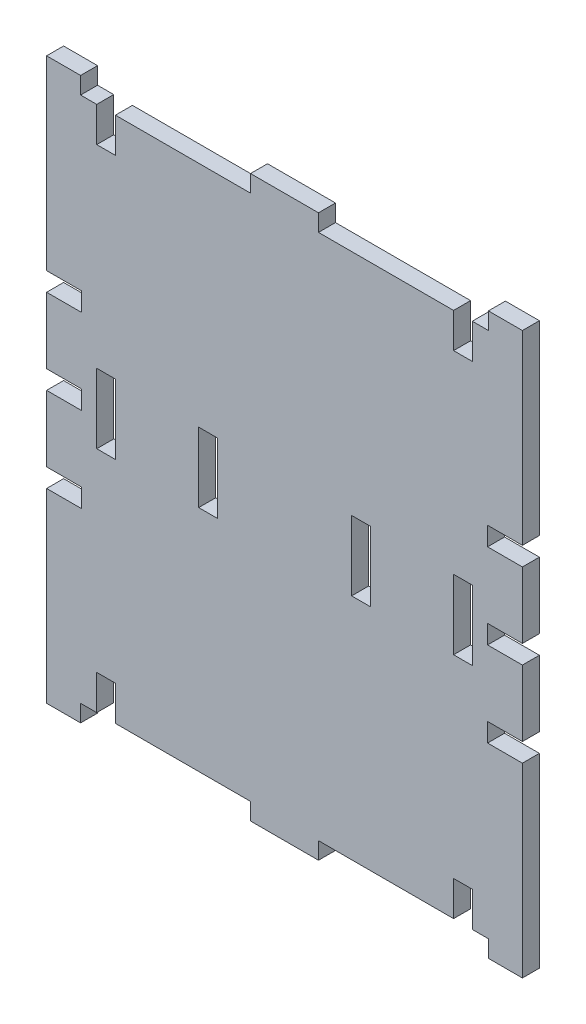
SolidWorks part; units mm, degrees
ref_plane "Front Plane" through (0, 0, 0) normal (0, 0, 1) x (1, 0, 0)
ref_plane "Top Plane" through (0, 0, 0) normal (0, 1, 0) x (1, 0, 0)
ref_plane "Right Plane" through (0, 0, 0) normal (1, 0, 0) x (0, 0, -1)
sketch "Model" plane through (0, 0, 0) normal (0, 0, 1) x (1, 0, 0)
  line L0 (213.2957, -153.6912) -> (213.2957, -159.1912)
  line L1 (203.2957, -208.9412) -> (163.5457, -208.9412)
  line L2 (213.2957, -134.1912) -> (223.5457, -134.1912)
  line L3 (93.5457, -208.9412) -> (93.5457, -213.9412)
  line L4 (213.2957, -128.6912) -> (213.2957, -134.1912)
  line L5 (98.2957, -198.6912) -> (98.2957, -208.9412)
  line L6 (143.5457, -213.9412) -> (143.5457, -208.9412)
  line L7 (83.5457, -213.9412) -> (83.5457, -159.1912)
  line L8 (223.5457, -128.6912) -> (213.2957, -128.6912)
  line L9 (213.5457, -53.9412) -> (208.7957, -53.9412)
  line L10 (103.7957, -198.6912) -> (98.2957, -198.6912)
  line L11 (223.5457, -153.6912) -> (213.2957, -153.6912)
  line L12 (223.5457, -109.1912) -> (223.5457, -128.6912)
  line L13 (163.5457, -208.9412) -> (163.5457, -213.9412)
  line L14 (83.5457, -103.6912) -> (93.7957, -103.6912)
  line L15 (93.7957, -103.6912) -> (93.7957, -109.1912)
  line L16 (93.7957, -109.1912) -> (83.5457, -109.1912)
  line L17 (83.5457, -109.1912) -> (83.5457, -128.6912)
  line L18 (83.5457, -128.6912) -> (93.7957, -128.6912)
  line L19 (93.7957, -128.6912) -> (93.7957, -134.1912)
  line L20 (93.7957, -134.1912) -> (83.5457, -134.1912)
  line L21 (83.5457, -153.6912) -> (83.5457, -134.1912)
  line L22 (83.5457, -153.6912) -> (93.7957, -153.6912)
  line L23 (93.7957, -153.6912) -> (93.7957, -159.1912)
  line L24 (93.7957, -159.1912) -> (83.5457, -159.1912)
  line L25 (93.5457, -213.9412) -> (83.5457, -213.9412)
  line L26 (98.2957, -208.9412) -> (93.5457, -208.9412)
  line L27 (103.7957, -208.9412) -> (103.7957, -198.6912)
  line L28 (143.5457, -208.9412) -> (103.7957, -208.9412)
  line L29 (163.5457, -213.9412) -> (143.5457, -213.9412)
  line L30 (203.2957, -208.9412) -> (203.2957, -198.6912)
  line L31 (203.2957, -198.6912) -> (208.7957, -198.6912)
  line L32 (208.7957, -198.6912) -> (208.7957, -208.9412)
  line L33 (208.7957, -208.9412) -> (213.5457, -208.9412)
  line L34 (213.5457, -208.9412) -> (213.5457, -213.9412)
  line L35 (213.5457, -213.9412) -> (223.5457, -213.9412)
  line L36 (223.5457, -213.9412) -> (223.5457, -159.1912)
  line L37 (213.2957, -159.1912) -> (223.5457, -159.1912)
  line L38 (223.5457, -153.6912) -> (223.5457, -134.1912)
  line L39 (213.2957, -109.1912) -> (223.5457, -109.1912)
  line L40 (213.2957, -103.6912) -> (213.2957, -109.1912)
  line L41 (223.5457, -103.6912) -> (213.2957, -103.6912)
  line L42 (223.5457, -103.6912) -> (223.5457, -48.9412)
  line L43 (223.5457, -48.9412) -> (213.5457, -48.9412)
  line L44 (213.5457, -48.9412) -> (213.5457, -53.9412)
  line L45 (208.7957, -64.1912) -> (208.7957, -53.9412)
  line L46 (203.2957, -64.1912) -> (208.7957, -64.1912)
  line L47 (203.2957, -53.9412) -> (203.2957, -64.1912)
  line L48 (203.2957, -53.9412) -> (163.5457, -53.9412)
  line L49 (163.5457, -53.9412) -> (163.5457, -48.9412)
  line L50 (163.5457, -48.9412) -> (143.5457, -48.9412)
  line L51 (143.5457, -48.9412) -> (143.5457, -53.9412)
  line L52 (143.5457, -53.9412) -> (103.7957, -53.9412)
  line L53 (103.7957, -53.9412) -> (103.7957, -64.1912)
  line L54 (103.7957, -64.1912) -> (98.2957, -64.1912)
  line L55 (98.2957, -64.1912) -> (98.2957, -53.9412)
  line L56 (93.5457, -53.9412) -> (98.2957, -53.9412)
  line L57 (93.5457, -48.9412) -> (93.5457, -53.9412)
  line L58 (83.5457, -48.9412) -> (93.5457, -48.9412)
  line L59 (83.5457, -103.6912) -> (83.5457, -48.9412)
  line L60 (173.2957, -121.1912) -> (178.7957, -121.1912)
  line L61 (178.7957, -121.1912) -> (178.7957, -141.6912)
  line L62 (178.7957, -141.6912) -> (173.2957, -141.6912)
  line L63 (173.2957, -141.6912) -> (173.2957, -121.1912)
  line L64 (203.2957, -141.6912) -> (203.2957, -121.1912)
  line L65 (203.2957, -121.1912) -> (208.7957, -121.1912)
  line L66 (208.7957, -121.1912) -> (208.7957, -141.6912)
  line L67 (208.7957, -141.6912) -> (203.2957, -141.6912)
  line L68 (128.2957, -141.6912) -> (133.7957, -141.6912)
  line L69 (128.2957, -121.1912) -> (128.2957, -141.6912)
  line L70 (133.7957, -121.1912) -> (128.2957, -121.1912)
  line L71 (133.7957, -141.6912) -> (133.7957, -121.1912)
  line L72 (98.2957, -121.1912) -> (98.2957, -141.6912)
  line L73 (103.7957, -121.1912) -> (98.2957, -121.1912)
  line L74 (103.7957, -141.6912) -> (103.7957, -121.1912)
  line L75 (98.2957, -141.6912) -> (103.7957, -141.6912)
  line L76 (206.2957, -156.4412) -> (211.2957, -156.4412)
  line L77 (209.2957, -157.4412) -> (211.2957, -156.4412)
  line L78 (209.2957, -155.4412) -> (211.2957, -156.4412)
  line L79 (195.5539, -158.6386) -> (195.5539, -156.4408)
  line L80 (195.5539, -156.4408) -> (196.5717, -156.4408)
  line L81 (196.5717, -156.4408) -> (197.129, -156.5095)
  line L82 (197.129, -156.5095) -> (197.4646, -156.6156)
  line L83 (197.4646, -156.6156) -> (197.6379, -156.7498)
  line L84 (197.6379, -156.7498) -> (197.6956, -156.9028)
  line L85 (197.6956, -156.9028) -> (197.6956, -158.1578)
  line L86 (197.6956, -158.1578) -> (197.6749, -158.2566)
  line L87 (197.6749, -158.2566) -> (197.6129, -158.3467)
  line L88 (197.6129, -158.3467) -> (197.3647, -158.5012)
  line L89 (197.3647, -158.5012) -> (197.0041, -158.6043)
  line L90 (197.0041, -158.6043) -> (196.5717, -158.6386)
  line L91 (196.5717, -158.6386) -> (195.5539, -158.6386)
  line L92 (195.5539, -154.3307) -> (195.5539, -158.6386)
  line L93 (195.5539, -158.6386) -> (196.5717, -158.6386)
  line L94 (196.5717, -158.6386) -> (197.0041, -158.6043)
  line L95 (197.0041, -158.6043) -> (197.3647, -158.5013)
  line L96 (197.3647, -158.5013) -> (197.6129, -158.3467)
  line L97 (197.6129, -158.3467) -> (197.6749, -158.2566)
  line L98 (197.6749, -158.2566) -> (197.6956, -158.1579)
  line L99 (197.6956, -158.1579) -> (197.6956, -156.903)
  line L100 (197.6956, -156.903) -> (197.6379, -156.75)
  line L101 (197.6379, -156.75) -> (197.4646, -156.6158)
  line L102 (197.4646, -156.6158) -> (197.129, -156.5096)
  line L103 (197.129, -156.5096) -> (196.5717, -156.441)
  line L104 (196.5717, -156.441) -> (197.1227, -156.377)
  line L105 (197.1227, -156.377) -> (197.4646, -156.2724)
  line L106 (197.4646, -156.2724) -> (197.6379, -156.1335)
  line L107 (197.6379, -156.1335) -> (197.6956, -155.9789)
  line L108 (197.6956, -155.9789) -> (197.6956, -154.8115)
  line L109 (197.6956, -154.8115) -> (197.6749, -154.7178)
  line L110 (197.6749, -154.7178) -> (197.6129, -154.6304)
  line L111 (197.6129, -154.6304) -> (197.3647, -154.4743)
  line L112 (197.3647, -154.4743) -> (197.001, -154.3666)
  line L113 (197.001, -154.3666) -> (196.5717, -154.3307)
  line L114 (196.5717, -154.3307) -> (195.5539, -154.3307)
  line L115 (196.5717, -156.4412) -> (195.5539, -156.4412)
  line L116 (195.5539, -156.4412) -> (195.5539, -154.3307)
  line L117 (195.5539, -154.3307) -> (196.5717, -154.3307)
  line L118 (196.5717, -154.3307) -> (197.001, -154.3666)
  line L119 (197.001, -154.3666) -> (197.3647, -154.4743)
  line L120 (197.3647, -154.4743) -> (197.6129, -154.6304)
  line L121 (197.6129, -154.6304) -> (197.6749, -154.7178)
  line L122 (197.6749, -154.7178) -> (197.6956, -154.8115)
  line L123 (197.6956, -154.8115) -> (197.6956, -155.9791)
  line L124 (197.6956, -155.9791) -> (197.6379, -156.1336)
  line L125 (197.6379, -156.1336) -> (197.4646, -156.2726)
  line L126 (197.4646, -156.2726) -> (197.1227, -156.3772)
  line L127 (197.1227, -156.3772) -> (196.5717, -156.4412)
  line L128 (198.5509, -158.6386) -> (198.5509, -154.3307)
  line L129 (198.5509, -154.3307) -> (200.6801, -154.3307)
  line L130 (200.6801, -154.3307) -> (198.5509, -154.3307)
  line L131 (198.5509, -154.3307) -> (198.5509, -156.4597)
  line L132 (198.5509, -156.4597) -> (200.3804, -156.4597)
  line L133 (200.3804, -156.4597) -> (198.5509, -156.4597)
  line L134 (198.5509, -156.4597) -> (198.5509, -158.6386)
  line L135 (202.6718, -158.6386) -> (202.2308, -158.6035)
  line L136 (202.2308, -158.6035) -> (201.8694, -158.4981)
  line L137 (201.8694, -158.4981) -> (201.6282, -158.3428)
  line L138 (201.6282, -158.3428) -> (201.5679, -158.2541)
  line L139 (201.5679, -158.2541) -> (201.5479, -158.1579)
  line L140 (201.5479, -158.1579) -> (201.5679, -158.2541)
  line L141 (201.5679, -158.2541) -> (201.6282, -158.3428)
  line L142 (201.6282, -158.3428) -> (201.8694, -158.4981)
  line L143 (201.8694, -158.4981) -> (202.2308, -158.6035)
  line L144 (203.1127, -158.6035) -> (203.4741, -158.4981)
  line L145 (203.4741, -158.4981) -> (203.7153, -158.3428)
  line L146 (203.7153, -158.3428) -> (203.7756, -158.2541)
  line L147 (203.7756, -158.2541) -> (203.7957, -158.1579)
  line L148 (203.7957, -158.1579) -> (203.7957, -156.4472)
  line L149 (203.7957, -156.4472) -> (203.7756, -156.351)
  line L150 (203.7756, -156.351) -> (203.7153, -156.2622)
  line L151 (203.7153, -156.2622) -> (203.4741, -156.1069)
  line L152 (203.4741, -156.1069) -> (203.1127, -156.0015)
  line L153 (203.1127, -156.0015) -> (202.6718, -155.9664)
  line L154 (202.6718, -155.9664) -> (201.9974, -156.0663)
  line L155 (201.9974, -156.0663) -> (201.7664, -156.1928)
  line L156 (201.7664, -156.1928) -> (201.5479, -156.4472)
  line L157 (201.5479, -156.4472) -> (201.5479, -154.3307)
  line L158 (201.5479, -154.3307) -> (203.7207, -154.3307)
  line L159 (203.7207, -154.3307) -> (201.5479, -154.3307)
  line L160 (201.5479, -154.3307) -> (201.5479, -156.4472)
  line L161 (201.5479, -156.4472) -> (201.7664, -156.1928)
  line L162 (201.7664, -156.1928) -> (201.9974, -156.0663)
  line L163 (201.9974, -156.0663) -> (202.6718, -155.9664)
  line L164 (202.6718, -155.9664) -> (203.1127, -156.0015)
  line L165 (203.1127, -156.0015) -> (203.4741, -156.1069)
  line L166 (203.4741, -156.1069) -> (203.7153, -156.2622)
  line L167 (203.7153, -156.2622) -> (203.7756, -156.351)
  line L168 (203.7756, -156.351) -> (203.7957, -156.4472)
  line L169 (203.7957, -156.4472) -> (203.7957, -158.1579)
  line L170 (203.7957, -158.1579) -> (203.7756, -158.2541)
  line L171 (203.7756, -158.2541) -> (203.7153, -158.3428)
  line L172 (203.7153, -158.3428) -> (203.4741, -158.4981)
  line L173 (203.4741, -158.4981) -> (203.1127, -158.6035)
  line L174 (203.1127, -158.6035) -> (202.6718, -158.6386)
  line L175 (100.7957, -106.4412) -> (95.7957, -106.4412)
  line L176 (97.7957, -105.4412) -> (95.7957, -106.4412)
  line L177 (97.7957, -107.4412) -> (95.7957, -106.4412)
  line L178 (103.2957, -108.6386) -> (103.2957, -106.4408)
  line L179 (103.2957, -106.4408) -> (104.3134, -106.4408)
  line L180 (104.3134, -106.4408) -> (104.8707, -106.5095)
  line L181 (104.8707, -106.5095) -> (105.2063, -106.6156)
  line L182 (105.2063, -106.6156) -> (105.3796, -106.7498)
  line L183 (105.3796, -106.7498) -> (105.4373, -106.9028)
  line L184 (105.4373, -106.9028) -> (105.4373, -108.1578)
  line L185 (105.4373, -108.1578) -> (105.4166, -108.2566)
  line L186 (105.4166, -108.2566) -> (105.3546, -108.3467)
  line L187 (105.3546, -108.3467) -> (105.1064, -108.5012)
  line L188 (105.1064, -108.5012) -> (104.7458, -108.6043)
  line L189 (104.7458, -108.6043) -> (104.3134, -108.6386)
  line L190 (104.3134, -108.6386) -> (103.2957, -108.6386)
  line L191 (103.2957, -104.3307) -> (103.2957, -108.6386)
  line L192 (103.2957, -108.6386) -> (104.3134, -108.6386)
  line L193 (104.3134, -108.6386) -> (104.7458, -108.6043)
  line L194 (104.7458, -108.6043) -> (105.1064, -108.5013)
  line L195 (105.1064, -108.5013) -> (105.3546, -108.3467)
  line L196 (105.3546, -108.3467) -> (105.4166, -108.2566)
  line L197 (105.4166, -108.2566) -> (105.4373, -108.1579)
  line L198 (105.4373, -108.1579) -> (105.4373, -106.903)
  line L199 (105.4373, -106.903) -> (105.3796, -106.75)
  line L200 (105.3796, -106.75) -> (105.2063, -106.6158)
  line L201 (105.2063, -106.6158) -> (104.8707, -106.5096)
  line L202 (104.8707, -106.5096) -> (104.3134, -106.441)
  line L203 (104.3134, -106.441) -> (104.8644, -106.377)
  line L204 (104.8644, -106.377) -> (105.2063, -106.2724)
  line L205 (105.2063, -106.2724) -> (105.3796, -106.1335)
  line L206 (105.3796, -106.1335) -> (105.4373, -105.9789)
  line L207 (105.4373, -105.9789) -> (105.4373, -104.8115)
  line L208 (105.4373, -104.8115) -> (105.4166, -104.7178)
  line L209 (105.4166, -104.7178) -> (105.3546, -104.6304)
  line L210 (105.3546, -104.6304) -> (105.1064, -104.4743)
  line L211 (105.1064, -104.4743) -> (104.7427, -104.3666)
  line L212 (104.7427, -104.3666) -> (104.3134, -104.3307)
  line L213 (104.3134, -104.3307) -> (103.2957, -104.3307)
  line L214 (104.3134, -106.4412) -> (103.2957, -106.4412)
  line L215 (103.2957, -106.4412) -> (103.2957, -104.3307)
  line L216 (103.2957, -104.3307) -> (104.3134, -104.3307)
  line L217 (104.3134, -104.3307) -> (104.7427, -104.3666)
  line L218 (104.7427, -104.3666) -> (105.1064, -104.4743)
  line L219 (105.1064, -104.4743) -> (105.3546, -104.6304)
  line L220 (105.3546, -104.6304) -> (105.4166, -104.7178)
  line L221 (105.4166, -104.7178) -> (105.4373, -104.8115)
  line L222 (105.4373, -104.8115) -> (105.4373, -105.9791)
  line L223 (105.4373, -105.9791) -> (105.3796, -106.1336)
  line L224 (105.3796, -106.1336) -> (105.2063, -106.2726)
  line L225 (105.2063, -106.2726) -> (104.8644, -106.3772)
  line L226 (104.8644, -106.3772) -> (104.3134, -106.4412)
  line L227 (106.2926, -108.6386) -> (106.2926, -104.3307)
  line L228 (106.2926, -104.3307) -> (108.4218, -104.3307)
  line L229 (108.4218, -104.3307) -> (106.2926, -104.3307)
  line L230 (106.2926, -104.3307) -> (106.2926, -106.4597)
  line L231 (106.2926, -106.4597) -> (108.1221, -106.4597)
  line L232 (108.1221, -106.4597) -> (106.2926, -106.4597)
  line L233 (106.2926, -106.4597) -> (106.2926, -108.6386)
  line L234 (110.4135, -108.6386) -> (109.9725, -108.6035)
  line L235 (109.9725, -108.6035) -> (109.6111, -108.4981)
  line L236 (109.6111, -108.4981) -> (109.3699, -108.3428)
  line L237 (109.3699, -108.3428) -> (109.3097, -108.2541)
  line L238 (109.3097, -108.2541) -> (109.2896, -108.1579)
  line L239 (109.2896, -108.1579) -> (109.3097, -108.2541)
  line L240 (109.3097, -108.2541) -> (109.3699, -108.3428)
  line L241 (109.3699, -108.3428) -> (109.6111, -108.4981)
  line L242 (109.6111, -108.4981) -> (109.9725, -108.6035)
  line L243 (110.8545, -108.6035) -> (111.2158, -108.4981)
  line L244 (111.2158, -108.4981) -> (111.457, -108.3428)
  line L245 (111.457, -108.3428) -> (111.5173, -108.2541)
  line L246 (111.5173, -108.2541) -> (111.5374, -108.1579)
  line L247 (111.5374, -108.1579) -> (111.5374, -106.4472)
  line L248 (111.5374, -106.4472) -> (111.5173, -106.351)
  line L249 (111.5173, -106.351) -> (111.457, -106.2622)
  line L250 (111.457, -106.2622) -> (111.2158, -106.1069)
  line L251 (111.2158, -106.1069) -> (110.8545, -106.0015)
  line L252 (110.8545, -106.0015) -> (110.4135, -105.9664)
  line L253 (110.4135, -105.9664) -> (109.7391, -106.0663)
  line L254 (109.7391, -106.0663) -> (109.5081, -106.1928)
  line L255 (109.5081, -106.1928) -> (109.2896, -106.4472)
  line L256 (109.2896, -106.4472) -> (109.2896, -104.3307)
  line L257 (109.2896, -104.3307) -> (111.4624, -104.3307)
  line L258 (111.4624, -104.3307) -> (109.2896, -104.3307)
  line L259 (109.2896, -104.3307) -> (109.2896, -106.4472)
  line L260 (109.2896, -106.4472) -> (109.5081, -106.1928)
  line L261 (109.5081, -106.1928) -> (109.7391, -106.0663)
  line L262 (109.7391, -106.0663) -> (110.4135, -105.9664)
  line L263 (110.4135, -105.9664) -> (110.8545, -106.0015)
  line L264 (110.8545, -106.0015) -> (111.2158, -106.1069)
  line L265 (111.2158, -106.1069) -> (111.457, -106.2622)
  line L266 (111.457, -106.2622) -> (111.5173, -106.351)
  line L267 (111.5173, -106.351) -> (111.5374, -106.4472)
  line L268 (111.5374, -106.4472) -> (111.5374, -108.1579)
  line L269 (111.5374, -108.1579) -> (111.5173, -108.2541)
  line L270 (111.5173, -108.2541) -> (111.457, -108.3428)
  line L271 (111.457, -108.3428) -> (111.2158, -108.4981)
  line L272 (111.2158, -108.4981) -> (110.8545, -108.6035)
  line L273 (110.8545, -108.6035) -> (110.4135, -108.6386)
  line L274 (100.7957, -156.4412) -> (95.7957, -156.4412)
  line L275 (97.7957, -155.4412) -> (95.7957, -156.4412)
  line L276 (97.7957, -157.4412) -> (95.7957, -156.4412)
  line L277 (103.2957, -158.6386) -> (103.2957, -156.4408)
  line L278 (103.2957, -156.4408) -> (104.3134, -156.4408)
  line L279 (104.3134, -156.4408) -> (104.8707, -156.5095)
  line L280 (104.8707, -156.5095) -> (105.2063, -156.6156)
  line L281 (105.2063, -156.6156) -> (105.3796, -156.7498)
  line L282 (105.3796, -156.7498) -> (105.4373, -156.9028)
  line L283 (105.4373, -156.9028) -> (105.4373, -158.1578)
  line L284 (105.4373, -158.1578) -> (105.4166, -158.2566)
  line L285 (105.4166, -158.2566) -> (105.3546, -158.3467)
  line L286 (105.3546, -158.3467) -> (105.1064, -158.5012)
  line L287 (105.1064, -158.5012) -> (104.7458, -158.6043)
  line L288 (104.7458, -158.6043) -> (104.3134, -158.6386)
  line L289 (104.3134, -158.6386) -> (103.2957, -158.6386)
  line L290 (103.2957, -154.3307) -> (103.2957, -158.6386)
  line L291 (103.2957, -158.6386) -> (104.3134, -158.6386)
  line L292 (104.3134, -158.6386) -> (104.7458, -158.6043)
  line L293 (104.7458, -158.6043) -> (105.1064, -158.5013)
  line L294 (105.1064, -158.5013) -> (105.3546, -158.3467)
  line L295 (105.3546, -158.3467) -> (105.4166, -158.2566)
  line L296 (105.4166, -158.2566) -> (105.4373, -158.1579)
  line L297 (105.4373, -158.1579) -> (105.4373, -156.903)
  line L298 (105.4373, -156.903) -> (105.3796, -156.75)
  line L299 (105.3796, -156.75) -> (105.2063, -156.6158)
  line L300 (105.2063, -156.6158) -> (104.8707, -156.5096)
  line L301 (104.8707, -156.5096) -> (104.3134, -156.441)
  line L302 (104.3134, -156.441) -> (104.8644, -156.377)
  line L303 (104.8644, -156.377) -> (105.2063, -156.2724)
  line L304 (105.2063, -156.2724) -> (105.3796, -156.1335)
  line L305 (105.3796, -156.1335) -> (105.4373, -155.9789)
  line L306 (105.4373, -155.9789) -> (105.4373, -154.8115)
  line L307 (105.4373, -154.8115) -> (105.4166, -154.7178)
  line L308 (105.4166, -154.7178) -> (105.3546, -154.6304)
  line L309 (105.3546, -154.6304) -> (105.1064, -154.4743)
  line L310 (105.1064, -154.4743) -> (104.7427, -154.3666)
  line L311 (104.7427, -154.3666) -> (104.3134, -154.3307)
  line L312 (104.3134, -154.3307) -> (103.2957, -154.3307)
  line L313 (104.3134, -156.4412) -> (103.2957, -156.4412)
  line L314 (103.2957, -156.4412) -> (103.2957, -154.3307)
  line L315 (103.2957, -154.3307) -> (104.3134, -154.3307)
  line L316 (104.3134, -154.3307) -> (104.7427, -154.3666)
  line L317 (104.7427, -154.3666) -> (105.1064, -154.4743)
  line L318 (105.1064, -154.4743) -> (105.3546, -154.6304)
  line L319 (105.3546, -154.6304) -> (105.4166, -154.7178)
  line L320 (105.4166, -154.7178) -> (105.4373, -154.8115)
  line L321 (105.4373, -154.8115) -> (105.4373, -155.9791)
  line L322 (105.4373, -155.9791) -> (105.3796, -156.1336)
  line L323 (105.3796, -156.1336) -> (105.2063, -156.2726)
  line L324 (105.2063, -156.2726) -> (104.8644, -156.3772)
  line L325 (104.8644, -156.3772) -> (104.3134, -156.4412)
  line L326 (106.2926, -158.6386) -> (106.2926, -154.3307)
  line L327 (106.2926, -154.3307) -> (108.4218, -154.3307)
  line L328 (108.4218, -154.3307) -> (106.2926, -154.3307)
  line L329 (106.2926, -154.3307) -> (106.2926, -156.4597)
  line L330 (106.2926, -156.4597) -> (108.1221, -156.4597)
  line L331 (108.1221, -156.4597) -> (106.2926, -156.4597)
  line L332 (106.2926, -156.4597) -> (106.2926, -158.6386)
  line L333 (110.4135, -158.6386) -> (109.9725, -158.6035)
  line L334 (109.9725, -158.6035) -> (109.6111, -158.4981)
  line L335 (109.6111, -158.4981) -> (109.3699, -158.3428)
  line L336 (109.3699, -158.3428) -> (109.3097, -158.2541)
  line L337 (109.3097, -158.2541) -> (109.2896, -158.1579)
  line L338 (109.2896, -158.1579) -> (109.3097, -158.2541)
  line L339 (109.3097, -158.2541) -> (109.3699, -158.3428)
  line L340 (109.3699, -158.3428) -> (109.6111, -158.4981)
  line L341 (109.6111, -158.4981) -> (109.9725, -158.6035)
  line L342 (110.8545, -158.6035) -> (111.2158, -158.4981)
  line L343 (111.2158, -158.4981) -> (111.457, -158.3428)
  line L344 (111.457, -158.3428) -> (111.5173, -158.2541)
  line L345 (111.5173, -158.2541) -> (111.5374, -158.1579)
  line L346 (111.5374, -158.1579) -> (111.5374, -156.4472)
  line L347 (111.5374, -156.4472) -> (111.5173, -156.351)
  line L348 (111.5173, -156.351) -> (111.457, -156.2622)
  line L349 (111.457, -156.2622) -> (111.2158, -156.1069)
  line L350 (111.2158, -156.1069) -> (110.8545, -156.0015)
  line L351 (110.8545, -156.0015) -> (110.4135, -155.9664)
  line L352 (110.4135, -155.9664) -> (109.7391, -156.0663)
  line L353 (109.7391, -156.0663) -> (109.5081, -156.1928)
  line L354 (109.5081, -156.1928) -> (109.2896, -156.4472)
  line L355 (109.2896, -156.4472) -> (109.2896, -154.3307)
  line L356 (109.2896, -154.3307) -> (111.4624, -154.3307)
  line L357 (111.4624, -154.3307) -> (109.2896, -154.3307)
  line L358 (109.2896, -154.3307) -> (109.2896, -156.4472)
  line L359 (109.2896, -156.4472) -> (109.5081, -156.1928)
  line L360 (109.5081, -156.1928) -> (109.7391, -156.0663)
  line L361 (109.7391, -156.0663) -> (110.4135, -155.9664)
  line L362 (110.4135, -155.9664) -> (110.8545, -156.0015)
  line L363 (110.8545, -156.0015) -> (111.2158, -156.1069)
  line L364 (111.2158, -156.1069) -> (111.457, -156.2622)
  line L365 (111.457, -156.2622) -> (111.5173, -156.351)
  line L366 (111.5173, -156.351) -> (111.5374, -156.4472)
  line L367 (111.5374, -156.4472) -> (111.5374, -158.1579)
  line L368 (111.5374, -158.1579) -> (111.5173, -158.2541)
  line L369 (111.5173, -158.2541) -> (111.457, -158.3428)
  line L370 (111.457, -158.3428) -> (111.2158, -158.4981)
  line L371 (111.2158, -158.4981) -> (110.8545, -158.6035)
  line L372 (110.8545, -158.6035) -> (110.4135, -158.6386)
  line L373 (149.4248, -133.6287) -> (149.4248, -131.4308)
  line L374 (149.4248, -131.4308) -> (150.4426, -131.4308)
  line L375 (150.4426, -131.4308) -> (150.9998, -131.4995)
  line L376 (150.9998, -131.4995) -> (151.3354, -131.6057)
  line L377 (151.3354, -131.6057) -> (151.5087, -131.7399)
  line L378 (151.5087, -131.7399) -> (151.5665, -131.8929)
  line L379 (151.5665, -131.8929) -> (151.5665, -133.1479)
  line L380 (151.5665, -133.1479) -> (151.5458, -133.2466)
  line L381 (151.5458, -133.2466) -> (151.4837, -133.3368)
  line L382 (151.4837, -133.3368) -> (151.2355, -133.4913)
  line L383 (151.2355, -133.4913) -> (150.875, -133.5943)
  line L384 (150.875, -133.5943) -> (150.4426, -133.6287)
  line L385 (150.4426, -133.6287) -> (149.4248, -133.6287)
  line L386 (149.4248, -129.3207) -> (149.4248, -133.6287)
  line L387 (149.4248, -133.6287) -> (150.4426, -133.6287)
  line L388 (150.4426, -133.6287) -> (150.875, -133.5943)
  line L389 (150.875, -133.5943) -> (151.2355, -133.4913)
  line L390 (151.2355, -133.4913) -> (151.4837, -133.3368)
  line L391 (151.4837, -133.3368) -> (151.5458, -133.2466)
  line L392 (151.5458, -133.2466) -> (151.5665, -133.1479)
  line L393 (151.5665, -133.1479) -> (151.5665, -131.893)
  line L394 (151.5665, -131.893) -> (151.5087, -131.7401)
  line L395 (151.5087, -131.7401) -> (151.3354, -131.6058)
  line L396 (151.3354, -131.6058) -> (150.9998, -131.4997)
  line L397 (150.9998, -131.4997) -> (150.4426, -131.431)
  line L398 (150.4426, -131.431) -> (150.9936, -131.367)
  line L399 (150.9936, -131.367) -> (151.3354, -131.2624)
  line L400 (151.3354, -131.2624) -> (151.5087, -131.1235)
  line L401 (151.5087, -131.1235) -> (151.5665, -130.969)
  line L402 (151.5665, -130.969) -> (151.5665, -129.8015)
  line L403 (151.5665, -129.8015) -> (151.5458, -129.7078)
  line L404 (151.5458, -129.7078) -> (151.4837, -129.6204)
  line L405 (151.4837, -129.6204) -> (151.2355, -129.4643)
  line L406 (151.2355, -129.4643) -> (150.8718, -129.3566)
  line L407 (150.8718, -129.3566) -> (150.4426, -129.3207)
  line L408 (150.4426, -129.3207) -> (149.4248, -129.3207)
  line L409 (150.4426, -131.4312) -> (149.4248, -131.4312)
  line L410 (149.4248, -131.4312) -> (149.4248, -129.3207)
  line L411 (149.4248, -129.3207) -> (150.4426, -129.3207)
  line L412 (150.4426, -129.3207) -> (150.8718, -129.3566)
  line L413 (150.8718, -129.3566) -> (151.2355, -129.4644)
  line L414 (151.2355, -129.4644) -> (151.4837, -129.6205)
  line L415 (151.4837, -129.6205) -> (151.5458, -129.7079)
  line L416 (151.5458, -129.7079) -> (151.5665, -129.8015)
  line L417 (151.5665, -129.8015) -> (151.5665, -130.9691)
  line L418 (151.5665, -130.9691) -> (151.5087, -131.1237)
  line L419 (151.5087, -131.1237) -> (151.3354, -131.2626)
  line L420 (151.3354, -131.2626) -> (150.9936, -131.3672)
  line L421 (150.9936, -131.3672) -> (150.4426, -131.4312)
  line L422 (152.4218, -133.6287) -> (152.4218, -129.3207)
  line L423 (152.4218, -129.3207) -> (154.5509, -129.3207)
  line L424 (154.5509, -129.3207) -> (152.4218, -129.3207)
  line L425 (152.4218, -129.3207) -> (152.4218, -131.4123)
  line L426 (152.4218, -131.4123) -> (154.2512, -131.4123)
  line L427 (154.2512, -131.4123) -> (152.4218, -131.4123)
  line L428 (152.4218, -131.4123) -> (152.4218, -133.6287)
  line L429 (152.4218, -133.6287) -> (154.5509, -133.6287)
  line L430 (154.5509, -133.6287) -> (152.4218, -133.6287)
  line L431 (156.5426, -133.6287) -> (156.1016, -133.5935)
  line L432 (156.1016, -133.5935) -> (155.7403, -133.4882)
  line L433 (155.7403, -133.4882) -> (155.4991, -133.3329)
  line L434 (155.4991, -133.3329) -> (155.4388, -133.2441)
  line L435 (155.4388, -133.2441) -> (155.4187, -133.1479)
  line L436 (155.4187, -133.1479) -> (155.4388, -133.2441)
  line L437 (155.4388, -133.2441) -> (155.4991, -133.3329)
  line L438 (155.4991, -133.3329) -> (155.7403, -133.4882)
  line L439 (155.7403, -133.4882) -> (156.1016, -133.5935)
  line L440 (156.9836, -133.5935) -> (157.345, -133.4882)
  line L441 (157.345, -133.4882) -> (157.5861, -133.3329)
  line L442 (157.5861, -133.3329) -> (157.6464, -133.2441)
  line L443 (157.6464, -133.2441) -> (157.6665, -133.1479)
  line L444 (157.6665, -133.1479) -> (157.6665, -131.4373)
  line L445 (157.6665, -131.4373) -> (157.6464, -131.3411)
  line L446 (157.6464, -131.3411) -> (157.5861, -131.2523)
  line L447 (157.5861, -131.2523) -> (157.345, -131.0969)
  line L448 (157.345, -131.0969) -> (156.9836, -130.9916)
  line L449 (156.9836, -130.9916) -> (156.5426, -130.9565)
  line L450 (156.5426, -130.9565) -> (155.8683, -131.0564)
  line L451 (155.8683, -131.0564) -> (155.6372, -131.1828)
  line L452 (155.6372, -131.1828) -> (155.4187, -131.4373)
  line L453 (155.4187, -131.4373) -> (155.4187, -129.3207)
  line L454 (155.4187, -129.3207) -> (157.5916, -129.3207)
  line L455 (157.5916, -129.3207) -> (155.4187, -129.3207)
  line L456 (155.4187, -129.3207) -> (155.4187, -131.4373)
  line L457 (155.4187, -131.4373) -> (155.6372, -131.1828)
  line L458 (155.6372, -131.1828) -> (155.8683, -131.0564)
  line L459 (155.8683, -131.0564) -> (156.5426, -130.9565)
  line L460 (156.5426, -130.9565) -> (156.9836, -130.9916)
  line L461 (156.9836, -130.9916) -> (157.345, -131.0969)
  line L462 (157.345, -131.0969) -> (157.5861, -131.2523)
  line L463 (157.5861, -131.2523) -> (157.6464, -131.3411)
  line L464 (157.6464, -131.3411) -> (157.6665, -131.4373)
  line L465 (157.6665, -131.4373) -> (157.6665, -133.1479)
  line L466 (157.6665, -133.1479) -> (157.6464, -133.2441)
  line L467 (157.6464, -133.2441) -> (157.5861, -133.3329)
  line L468 (157.5861, -133.3329) -> (157.345, -133.4882)
  line L469 (157.345, -133.4882) -> (156.9836, -133.5935)
  line L470 (156.9836, -133.5935) -> (156.5426, -133.6287)
  line L471 (146.9248, -131.4412) -> (141.9248, -131.4412)
  line L472 (143.9248, -130.4412) -> (141.9248, -131.4412)
  line L473 (143.9248, -132.4412) -> (141.9248, -131.4412)
  line L474 (160.1665, -131.4412) -> (165.1665, -131.4412)
  line L475 (163.1665, -132.4412) -> (165.1665, -131.4412)
  line L476 (163.1665, -130.4412) -> (165.1665, -131.4412)
  line L477 (206.2957, -106.4412) -> (211.2957, -106.4412)
  line L478 (209.2957, -107.4412) -> (211.2957, -106.4412)
  line L479 (209.2957, -105.4412) -> (211.2957, -106.4412)
  line L480 (195.5539, -108.6386) -> (195.5539, -106.4408)
  line L481 (195.5539, -106.4408) -> (196.5717, -106.4408)
  line L482 (196.5717, -106.4408) -> (197.129, -106.5095)
  line L483 (197.129, -106.5095) -> (197.4646, -106.6156)
  line L484 (197.4646, -106.6156) -> (197.6379, -106.7498)
  line L485 (197.6379, -106.7498) -> (197.6956, -106.9028)
  line L486 (197.6956, -106.9028) -> (197.6956, -108.1578)
  line L487 (197.6956, -108.1578) -> (197.6749, -108.2566)
  line L488 (197.6749, -108.2566) -> (197.6129, -108.3467)
  line L489 (197.6129, -108.3467) -> (197.3647, -108.5012)
  line L490 (197.3647, -108.5012) -> (197.0041, -108.6043)
  line L491 (197.0041, -108.6043) -> (196.5717, -108.6386)
  line L492 (196.5717, -108.6386) -> (195.5539, -108.6386)
  line L493 (195.5539, -104.3307) -> (195.5539, -108.6386)
  line L494 (195.5539, -108.6386) -> (196.5717, -108.6386)
  line L495 (196.5717, -108.6386) -> (197.0041, -108.6043)
  line L496 (197.0041, -108.6043) -> (197.3647, -108.5013)
  line L497 (197.3647, -108.5013) -> (197.6129, -108.3467)
  line L498 (197.6129, -108.3467) -> (197.6749, -108.2566)
  line L499 (197.6749, -108.2566) -> (197.6956, -108.1579)
  line L500 (197.6956, -108.1579) -> (197.6956, -106.903)
  line L501 (197.6956, -106.903) -> (197.6379, -106.75)
  line L502 (197.6379, -106.75) -> (197.4646, -106.6158)
  line L503 (197.4646, -106.6158) -> (197.129, -106.5096)
  line L504 (197.129, -106.5096) -> (196.5717, -106.441)
  line L505 (196.5717, -106.441) -> (197.1227, -106.377)
  line L506 (197.1227, -106.377) -> (197.4646, -106.2724)
  line L507 (197.4646, -106.2724) -> (197.6379, -106.1335)
  line L508 (197.6379, -106.1335) -> (197.6956, -105.9789)
  line L509 (197.6956, -105.9789) -> (197.6956, -104.8115)
  line L510 (197.6956, -104.8115) -> (197.6749, -104.7178)
  line L511 (197.6749, -104.7178) -> (197.6129, -104.6304)
  line L512 (197.6129, -104.6304) -> (197.3647, -104.4743)
  line L513 (197.3647, -104.4743) -> (197.001, -104.3666)
  line L514 (197.001, -104.3666) -> (196.5717, -104.3307)
  line L515 (196.5717, -104.3307) -> (195.5539, -104.3307)
  line L516 (196.5717, -106.4412) -> (195.5539, -106.4412)
  line L517 (195.5539, -106.4412) -> (195.5539, -104.3307)
  line L518 (195.5539, -104.3307) -> (196.5717, -104.3307)
  line L519 (196.5717, -104.3307) -> (197.001, -104.3666)
  line L520 (197.001, -104.3666) -> (197.3647, -104.4743)
  line L521 (197.3647, -104.4743) -> (197.6129, -104.6304)
  line L522 (197.6129, -104.6304) -> (197.6749, -104.7178)
  line L523 (197.6749, -104.7178) -> (197.6956, -104.8115)
  line L524 (197.6956, -104.8115) -> (197.6956, -105.9791)
  line L525 (197.6956, -105.9791) -> (197.6379, -106.1336)
  line L526 (197.6379, -106.1336) -> (197.4646, -106.2726)
  line L527 (197.4646, -106.2726) -> (197.1227, -106.3772)
  line L528 (197.1227, -106.3772) -> (196.5717, -106.4412)
  line L529 (198.5509, -108.6386) -> (198.5509, -104.3307)
  line L530 (198.5509, -104.3307) -> (200.6801, -104.3307)
  line L531 (200.6801, -104.3307) -> (198.5509, -104.3307)
  line L532 (198.5509, -104.3307) -> (198.5509, -106.4597)
  line L533 (198.5509, -106.4597) -> (200.3804, -106.4597)
  line L534 (200.3804, -106.4597) -> (198.5509, -106.4597)
  line L535 (198.5509, -106.4597) -> (198.5509, -108.6386)
  line L536 (202.6718, -108.6386) -> (202.2308, -108.6035)
  line L537 (202.2308, -108.6035) -> (201.8694, -108.4981)
  line L538 (201.8694, -108.4981) -> (201.6282, -108.3428)
  line L539 (201.6282, -108.3428) -> (201.5679, -108.2541)
  line L540 (201.5679, -108.2541) -> (201.5479, -108.1579)
  line L541 (201.5479, -108.1579) -> (201.5679, -108.2541)
  line L542 (201.5679, -108.2541) -> (201.6282, -108.3428)
  line L543 (201.6282, -108.3428) -> (201.8694, -108.4981)
  line L544 (201.8694, -108.4981) -> (202.2308, -108.6035)
  line L545 (203.1127, -108.6035) -> (203.4741, -108.4981)
  line L546 (203.4741, -108.4981) -> (203.7153, -108.3428)
  line L547 (203.7153, -108.3428) -> (203.7756, -108.2541)
  line L548 (203.7756, -108.2541) -> (203.7957, -108.1579)
  line L549 (203.7957, -108.1579) -> (203.7957, -106.4472)
  line L550 (203.7957, -106.4472) -> (203.7756, -106.351)
  line L551 (203.7756, -106.351) -> (203.7153, -106.2622)
  line L552 (203.7153, -106.2622) -> (203.4741, -106.1069)
  line L553 (203.4741, -106.1069) -> (203.1127, -106.0015)
  line L554 (203.1127, -106.0015) -> (202.6718, -105.9664)
  line L555 (202.6718, -105.9664) -> (201.9974, -106.0663)
  line L556 (201.9974, -106.0663) -> (201.7664, -106.1928)
  line L557 (201.7664, -106.1928) -> (201.5479, -106.4472)
  line L558 (201.5479, -106.4472) -> (201.5479, -104.3307)
  line L559 (201.5479, -104.3307) -> (203.7207, -104.3307)
  line L560 (203.7207, -104.3307) -> (201.5479, -104.3307)
  line L561 (201.5479, -104.3307) -> (201.5479, -106.4472)
  line L562 (201.5479, -106.4472) -> (201.7664, -106.1928)
  line L563 (201.7664, -106.1928) -> (201.9974, -106.0663)
  line L564 (201.9974, -106.0663) -> (202.6718, -105.9664)
  line L565 (202.6718, -105.9664) -> (203.1127, -106.0015)
  line L566 (203.1127, -106.0015) -> (203.4741, -106.1069)
  line L567 (203.4741, -106.1069) -> (203.7153, -106.2622)
  line L568 (203.7153, -106.2622) -> (203.7756, -106.351)
  line L569 (203.7756, -106.351) -> (203.7957, -106.4472)
  line L570 (203.7957, -106.4472) -> (203.7957, -108.1579)
  line L571 (203.7957, -108.1579) -> (203.7756, -108.2541)
  line L572 (203.7756, -108.2541) -> (203.7153, -108.3428)
  line L573 (203.7153, -108.3428) -> (203.4741, -108.4981)
  line L574 (203.4741, -108.4981) -> (203.1127, -108.6035)
  line L575 (203.1127, -108.6035) -> (202.6718, -108.6386)
  line L576 (218.4207, -141.1912) -> (218.4207, -136.1912)
  line L577 (219.4207, -138.1912) -> (218.4207, -136.1912)
  line L578 (217.4207, -138.1912) -> (218.4207, -136.1912)
  line L579 (220.6181, -151.9329) -> (218.4203, -151.9329)
  line L580 (218.4203, -151.9329) -> (218.4203, -150.9151)
  line L581 (218.4203, -150.9151) -> (218.4889, -150.3579)
  line L582 (218.4889, -150.3579) -> (218.5951, -150.0222)
  line L583 (218.5951, -150.0222) -> (218.7293, -149.849)
  line L584 (218.7293, -149.849) -> (218.8823, -149.7912)
  line L585 (218.8823, -149.7912) -> (220.1373, -149.7912)
  line L586 (220.1373, -149.7912) -> (220.2361, -149.8119)
  line L587 (220.2361, -149.8119) -> (220.3262, -149.8739)
  line L588 (220.3262, -149.8739) -> (220.4807, -150.1221)
  line L589 (220.4807, -150.1221) -> (220.5838, -150.4827)
  line L590 (220.5838, -150.4827) -> (220.6181, -150.9151)
  line L591 (220.6181, -150.9151) -> (220.6181, -151.9329)
  line L592 (216.3102, -151.9329) -> (220.6181, -151.9329)
  line L593 (220.6181, -151.9329) -> (220.6181, -150.9151)
  line L594 (220.6181, -150.9151) -> (220.5838, -150.4827)
  line L595 (220.5838, -150.4827) -> (220.4808, -150.1221)
  line L596 (220.4808, -150.1221) -> (220.3262, -149.8739)
  line L597 (220.3262, -149.8739) -> (220.2361, -149.8119)
  line L598 (220.2361, -149.8119) -> (220.1374, -149.7912)
  line L599 (220.1374, -149.7912) -> (218.8825, -149.7912)
  line L600 (218.8825, -149.7912) -> (218.7295, -149.849)
  line L601 (218.7295, -149.849) -> (218.5953, -150.0222)
  line L602 (218.5953, -150.0222) -> (218.4891, -150.3579)
  line L603 (218.4891, -150.3579) -> (218.4205, -150.9151)
  line L604 (218.4205, -150.9151) -> (218.3565, -150.3641)
  line L605 (218.3565, -150.3641) -> (218.2519, -150.0222)
  line L606 (218.2519, -150.0222) -> (218.113, -149.849)
  line L607 (218.113, -149.849) -> (217.9584, -149.7912)
  line L608 (217.9584, -149.7912) -> (216.7909, -149.7912)
  line L609 (216.7909, -149.7912) -> (216.6973, -149.8119)
  line L610 (216.6973, -149.8119) -> (216.6099, -149.8739)
  line L611 (216.6099, -149.8739) -> (216.4538, -150.1221)
  line L612 (216.4538, -150.1221) -> (216.3461, -150.4859)
  line L613 (216.3461, -150.4859) -> (216.3102, -150.9151)
  line L614 (216.3102, -150.9151) -> (216.3102, -151.9329)
  line L615 (218.4207, -150.9151) -> (218.4207, -151.9329)
  line L616 (218.4207, -151.9329) -> (216.3102, -151.9329)
  line L617 (216.3102, -151.9329) -> (216.3102, -150.9151)
  line L618 (216.3102, -150.9151) -> (216.3461, -150.4859)
  line L619 (216.3461, -150.4859) -> (216.4538, -150.1221)
  line L620 (216.4538, -150.1221) -> (216.6099, -149.8739)
  line L621 (216.6099, -149.8739) -> (216.6973, -149.8119)
  line L622 (216.6973, -149.8119) -> (216.791, -149.7912)
  line L623 (216.791, -149.7912) -> (217.9586, -149.7912)
  line L624 (217.9586, -149.7912) -> (218.1131, -149.849)
  line L625 (218.1131, -149.849) -> (218.2521, -150.0222)
  line L626 (218.2521, -150.0222) -> (218.3566, -150.3641)
  line L627 (218.3566, -150.3641) -> (218.4207, -150.9151)
  line L628 (220.6181, -148.9359) -> (218.4203, -148.9359)
  line L629 (218.4203, -148.9359) -> (218.4203, -147.9182)
  line L630 (218.4203, -147.9182) -> (218.4889, -147.3609)
  line L631 (218.4889, -147.3609) -> (218.5951, -147.0253)
  line L632 (218.5951, -147.0253) -> (218.7293, -146.852)
  line L633 (218.7293, -146.852) -> (218.8823, -146.7943)
  line L634 (218.8823, -146.7943) -> (220.1373, -146.7943)
  line L635 (220.1373, -146.7943) -> (220.2361, -146.8149)
  line L636 (220.2361, -146.8149) -> (220.3262, -146.877)
  line L637 (220.3262, -146.877) -> (220.4807, -147.1252)
  line L638 (220.4807, -147.1252) -> (220.5838, -147.4858)
  line L639 (220.5838, -147.4858) -> (220.6181, -147.9182)
  line L640 (220.6181, -147.9182) -> (220.6181, -148.9359)
  line L641 (216.3102, -148.9359) -> (220.6181, -148.9359)
  line L642 (220.6181, -148.9359) -> (220.6181, -147.9182)
  line L643 (220.6181, -147.9182) -> (220.5838, -147.4858)
  line L644 (220.5838, -147.4858) -> (220.4808, -147.1252)
  line L645 (220.4808, -147.1252) -> (220.3262, -146.877)
  line L646 (220.3262, -146.877) -> (220.2361, -146.8149)
  line L647 (220.2361, -146.8149) -> (220.1374, -146.7943)
  line L648 (220.1374, -146.7943) -> (218.8825, -146.7943)
  line L649 (218.8825, -146.7943) -> (218.7295, -146.852)
  line L650 (218.7295, -146.852) -> (218.5953, -147.0253)
  line L651 (218.5953, -147.0253) -> (218.4891, -147.3609)
  line L652 (218.4891, -147.3609) -> (218.4205, -147.9182)
  line L653 (218.4205, -147.9182) -> (218.3565, -147.3672)
  line L654 (218.3565, -147.3672) -> (218.2519, -147.0253)
  line L655 (218.2519, -147.0253) -> (218.113, -146.852)
  line L656 (218.113, -146.852) -> (217.9584, -146.7943)
  line L657 (217.9584, -146.7943) -> (216.7909, -146.7943)
  line L658 (216.7909, -146.7943) -> (216.6973, -146.8149)
  line L659 (216.6973, -146.8149) -> (216.6099, -146.877)
  line L660 (216.6099, -146.877) -> (216.4538, -147.1252)
  line L661 (216.4538, -147.1252) -> (216.3461, -147.4889)
  line L662 (216.3461, -147.4889) -> (216.3102, -147.9182)
  line L663 (216.3102, -147.9182) -> (216.3102, -148.9359)
  line L664 (218.4207, -147.9182) -> (218.4207, -148.9359)
  line L665 (218.4207, -148.9359) -> (216.3102, -148.9359)
  line L666 (216.3102, -148.9359) -> (216.3102, -147.9182)
  line L667 (216.3102, -147.9182) -> (216.3461, -147.4889)
  line L668 (216.3461, -147.4889) -> (216.4538, -147.1252)
  line L669 (216.4538, -147.1252) -> (216.6099, -146.877)
  line L670 (216.6099, -146.877) -> (216.6973, -146.8149)
  line L671 (216.6973, -146.8149) -> (216.791, -146.7943)
  line L672 (216.791, -146.7943) -> (217.9586, -146.7943)
  line L673 (217.9586, -146.7943) -> (218.1131, -146.852)
  line L674 (218.1131, -146.852) -> (218.2521, -147.0253)
  line L675 (218.2521, -147.0253) -> (218.3566, -147.3672)
  line L676 (218.3566, -147.3672) -> (218.4207, -147.9182)
  line L677 (220.6181, -144.8151) -> (220.583, -145.2561)
  line L678 (220.583, -145.2561) -> (220.4776, -145.6174)
  line L679 (220.4776, -145.6174) -> (220.3223, -145.8586)
  line L680 (220.3223, -145.8586) -> (220.2335, -145.9189)
  line L681 (220.2335, -145.9189) -> (220.1374, -145.939)
  line L682 (220.1374, -145.939) -> (220.2335, -145.9189)
  line L683 (220.2335, -145.9189) -> (220.3223, -145.8586)
  line L684 (220.3223, -145.8586) -> (220.4776, -145.6174)
  line L685 (220.4776, -145.6174) -> (220.583, -145.2561)
  line L686 (220.583, -144.3741) -> (220.4776, -144.0127)
  line L687 (220.4776, -144.0127) -> (220.3223, -143.7716)
  line L688 (220.3223, -143.7716) -> (220.2335, -143.7113)
  line L689 (220.2335, -143.7113) -> (220.1374, -143.6912)
  line L690 (220.1374, -143.6912) -> (218.4267, -143.6912)
  line L691 (218.4267, -143.6912) -> (218.3305, -143.7113)
  line L692 (218.3305, -143.7113) -> (218.2417, -143.7716)
  line L693 (218.2417, -143.7716) -> (218.0864, -144.0127)
  line L694 (218.0864, -144.0127) -> (217.981, -144.3741)
  line L695 (217.981, -144.3741) -> (217.9459, -144.8151)
  line L696 (217.9459, -144.8151) -> (218.0458, -145.4894)
  line L697 (218.0458, -145.4894) -> (218.1723, -145.7205)
  line L698 (218.1723, -145.7205) -> (218.4267, -145.939)
  line L699 (218.4267, -145.939) -> (216.3102, -145.939)
  line L700 (216.3102, -145.939) -> (216.3102, -143.7661)
  line L701 (216.3102, -143.7661) -> (216.3102, -145.939)
  line L702 (216.3102, -145.939) -> (218.4267, -145.939)
  line L703 (218.4267, -145.939) -> (218.1723, -145.7205)
  line L704 (218.1723, -145.7205) -> (218.0458, -145.4894)
  line L705 (218.0458, -145.4894) -> (217.9459, -144.8151)
  line L706 (217.9459, -144.8151) -> (217.981, -144.3741)
  line L707 (217.981, -144.3741) -> (218.0864, -144.0127)
  line L708 (218.0864, -144.0127) -> (218.2417, -143.7716)
  line L709 (218.2417, -143.7716) -> (218.3305, -143.7113)
  line L710 (218.3305, -143.7113) -> (218.4267, -143.6912)
  line L711 (218.4267, -143.6912) -> (220.1374, -143.6912)
  line L712 (220.1374, -143.6912) -> (220.2335, -143.7113)
  line L713 (220.2335, -143.7113) -> (220.3223, -143.7716)
  line L714 (220.3223, -143.7716) -> (220.4776, -144.0127)
  line L715 (220.4776, -144.0127) -> (220.583, -144.3741)
  line L716 (220.583, -144.3741) -> (220.6181, -144.8151)
  line L717 (201.9248, -76.4991) -> (201.9248, -74.3013)
  line L718 (203.4998, -74.3699) -> (203.8354, -74.4761)
  line L719 (203.8354, -74.4761) -> (204.0087, -74.6103)
  line L720 (204.0087, -74.6103) -> (204.0665, -74.7633)
  line L721 (204.0665, -74.7633) -> (204.0665, -76.0183)
  line L722 (204.0665, -76.0183) -> (204.0458, -76.117)
  line L723 (204.0458, -76.117) -> (203.9837, -76.2072)
  line L724 (203.9837, -76.2072) -> (203.7355, -76.3617)
  line L725 (203.7355, -76.3617) -> (203.375, -76.4647)
  line L726 (203.375, -76.4647) -> (202.9426, -76.4991)
  line L727 (202.9426, -76.4991) -> (201.9248, -76.4991)
  line L728 (201.9248, -72.1912) -> (201.9248, -76.4991)
  line L729 (201.9248, -76.4991) -> (202.9426, -76.4991)
  line L730 (202.9426, -76.4991) -> (203.375, -76.4648)
  line L731 (203.375, -76.4648) -> (203.7355, -76.3618)
  line L732 (203.7355, -76.3618) -> (203.9837, -76.2072)
  line L733 (203.9837, -76.2072) -> (204.0458, -76.1171)
  line L734 (204.0458, -76.1171) -> (204.0665, -76.0183)
  line L735 (204.0665, -76.0183) -> (204.0665, -74.7634)
  line L736 (204.0665, -74.7634) -> (204.0087, -74.6105)
  line L737 (204.0087, -74.6105) -> (203.8354, -74.4763)
  line L738 (203.8354, -74.4763) -> (203.4998, -74.3699)
  line L739 (203.4998, -74.3699) -> (202.9426, -74.3013)
  line L740 (203.4936, -74.2375) -> (203.8354, -74.1329)
  line L741 (203.8354, -74.1329) -> (204.0087, -73.9939)
  line L742 (204.0087, -73.9939) -> (204.0665, -73.8394)
  line L743 (204.0665, -73.8394) -> (204.0665, -72.6719)
  line L744 (204.0665, -72.6719) -> (204.0458, -72.5783)
  line L745 (204.0458, -72.5783) -> (203.9837, -72.4909)
  line L746 (203.9837, -72.4909) -> (203.7355, -72.3347)
  line L747 (203.7355, -72.3347) -> (203.3718, -72.2271)
  line L748 (203.3718, -72.2271) -> (202.9426, -72.1912)
  line L749 (202.9426, -72.1912) -> (201.9248, -72.1912)
  line L750 (202.9426, -74.3013) -> (201.9248, -74.3013)
  line L751 (201.9248, -74.3013) -> (201.9248, -72.1912)
  line L752 (201.9248, -72.1912) -> (202.9426, -72.1912)
  line L753 (202.9426, -72.1912) -> (203.3718, -72.2271)
  line L754 (203.3718, -72.2271) -> (203.7355, -72.3348)
  line L755 (203.7355, -72.3348) -> (203.9837, -72.4909)
  line L756 (203.9837, -72.4909) -> (204.0458, -72.5783)
  line L757 (204.0458, -72.5783) -> (204.0665, -72.672)
  line L758 (204.0665, -72.672) -> (204.0665, -73.8396)
  line L759 (204.0665, -73.8396) -> (204.0087, -73.9941)
  line L760 (204.0087, -73.9941) -> (203.8354, -74.133)
  line L761 (203.8354, -74.133) -> (203.4936, -74.2375)
  line L762 (203.4936, -74.2375) -> (202.9426, -74.3013)
  line L763 (205.9832, -72.1851) -> (206.5349, -74.3016)
  line L764 (205.9832, -72.1851) -> (205.4624, -74.3016)
  line L765 (206.6326, -74.6821) -> (207.1071, -76.4991)
  line L766 (208.6016, -76.464) -> (208.2403, -76.3586)
  line L767 (208.2403, -76.3586) -> (207.9991, -76.2033)
  line L768 (207.9991, -76.2033) -> (207.9388, -76.1145)
  line L769 (207.9388, -76.1145) -> (207.9187, -76.0183)
  line L770 (207.9187, -76.0183) -> (207.9388, -76.1145)
  line L771 (207.9388, -76.1145) -> (207.9991, -76.2033)
  line L772 (207.9991, -76.2033) -> (208.2403, -76.3586)
  line L773 (208.2403, -76.3586) -> (208.6016, -76.464)
  line L774 (209.4836, -76.464) -> (209.845, -76.3586)
  line L775 (209.845, -76.3586) -> (210.0861, -76.2033)
  line L776 (210.0861, -76.2033) -> (210.1464, -76.1145)
  line L777 (210.1464, -76.1145) -> (210.1665, -76.0183)
  line L778 (210.1665, -76.0183) -> (210.1665, -74.3077)
  line L779 (210.1665, -74.3077) -> (210.1464, -74.2115)
  line L780 (210.1464, -74.2115) -> (210.0861, -74.1227)
  line L781 (210.0861, -74.1227) -> (209.845, -73.9674)
  line L782 (209.845, -73.9674) -> (209.4836, -73.862)
  line L783 (209.4836, -73.862) -> (209.0426, -73.8269)
  line L784 (209.0426, -73.8269) -> (208.3683, -73.9268)
  line L785 (208.3683, -73.9268) -> (208.1372, -74.0532)
  line L786 (208.1372, -74.0532) -> (207.9187, -74.3077)
  line L787 (207.9187, -74.3077) -> (207.9187, -72.1912)
  line L788 (207.9187, -72.1912) -> (210.0916, -72.1912)
  line L789 (210.0916, -72.1912) -> (207.9187, -72.1912)
  line L790 (207.9187, -72.1912) -> (207.9187, -74.3077)
  line L791 (207.9187, -74.3077) -> (208.1372, -74.0532)
  line L792 (208.1372, -74.0532) -> (208.3683, -73.9268)
  line L793 (208.3683, -73.9268) -> (209.0426, -73.8269)
  line L794 (209.0426, -73.8269) -> (209.4836, -73.862)
  line L795 (209.4836, -73.862) -> (209.845, -73.9674)
  line L796 (209.845, -73.9674) -> (210.0861, -74.1227)
  line L797 (210.0861, -74.1227) -> (210.1464, -74.2115)
  line L798 (210.1464, -74.2115) -> (210.1665, -74.3077)
  line L799 (210.1665, -74.3077) -> (210.1665, -76.0183)
  line L800 (210.1665, -76.0183) -> (210.1464, -76.1145)
  line L801 (210.1464, -76.1145) -> (210.0861, -76.2033)
  line L802 (210.0861, -76.2033) -> (209.845, -76.3586)
  line L803 (209.845, -76.3586) -> (209.4836, -76.464)
  line L804 (209.4836, -76.464) -> (209.0426, -76.4991)
  line L805 (209.0426, -76.4991) -> (208.6016, -76.464)
  line L806 (206.5349, -74.3016) -> (206.6326, -74.6764)
  line L807 (205.4624, -74.3016) -> (204.9218, -76.4991)
  line L808 (205.4624, -74.3016) -> (206.5349, -74.3016)
  line L809 (206.0457, -71.1912) -> (206.0457, -66.1912)
  line L810 (207.0457, -68.1912) -> (206.0457, -66.1912)
  line L811 (205.0457, -68.1912) -> (206.0457, -66.1912)
  line L812 (215.4233, -61.2491) -> (215.4233, -59.0513)
  line L813 (215.4233, -59.0513) -> (216.441, -59.0513)
  line L814 (216.441, -59.0513) -> (216.9983, -59.1199)
  line L815 (216.9983, -59.1199) -> (217.3339, -59.2261)
  line L816 (217.3339, -59.2261) -> (217.5072, -59.3603)
  line L817 (217.5072, -59.3603) -> (217.565, -59.5133)
  line L818 (217.565, -59.5133) -> (217.565, -60.7683)
  line L819 (217.565, -60.7683) -> (217.5443, -60.867)
  line L820 (217.5443, -60.867) -> (217.4822, -60.9572)
  line L821 (217.4822, -60.9572) -> (217.234, -61.1117)
  line L822 (217.234, -61.1117) -> (216.8734, -61.2147)
  line L823 (216.8734, -61.2147) -> (216.441, -61.2491)
  line L824 (216.441, -61.2491) -> (215.4233, -61.2491)
  line L825 (215.4233, -56.9412) -> (215.4233, -61.2491)
  line L826 (215.4233, -61.2491) -> (216.441, -61.2491)
  line L827 (216.441, -61.2491) -> (216.8734, -61.2148)
  line L828 (216.8734, -61.2148) -> (217.234, -61.1118)
  line L829 (217.234, -61.1118) -> (217.4822, -60.9572)
  line L830 (217.4822, -60.9572) -> (217.5443, -60.8671)
  line L831 (217.5443, -60.8671) -> (217.565, -60.7683)
  line L832 (217.565, -60.7683) -> (217.565, -59.5134)
  line L833 (217.565, -59.5134) -> (217.5072, -59.3605)
  line L834 (217.5072, -59.3605) -> (217.3339, -59.2263)
  line L835 (217.3339, -59.2263) -> (216.9983, -59.1201)
  line L836 (216.9983, -59.1201) -> (216.441, -59.0514)
  line L837 (216.441, -59.0514) -> (216.9921, -58.9875)
  line L838 (216.9921, -58.9875) -> (217.3339, -58.8829)
  line L839 (217.3339, -58.8829) -> (217.5072, -58.7439)
  line L840 (217.5072, -58.7439) -> (217.565, -58.5894)
  line L841 (217.565, -58.5894) -> (217.565, -57.4219)
  line L842 (217.565, -57.4219) -> (217.5443, -57.3283)
  line L843 (217.5443, -57.3283) -> (217.4822, -57.2409)
  line L844 (217.4822, -57.2409) -> (217.234, -57.0847)
  line L845 (217.234, -57.0847) -> (216.8703, -56.9771)
  line L846 (216.8703, -56.9771) -> (216.441, -56.9412)
  line L847 (216.441, -56.9412) -> (215.4233, -56.9412)
  line L848 (216.441, -59.0516) -> (215.4233, -59.0516)
  line L849 (215.4233, -59.0516) -> (215.4233, -56.9412)
  line L850 (215.4233, -56.9412) -> (216.441, -56.9412)
  line L851 (216.441, -56.9412) -> (216.8703, -56.9771)
  line L852 (216.8703, -56.9771) -> (217.234, -57.0848)
  line L853 (217.234, -57.0848) -> (217.4822, -57.2409)
  line L854 (217.4822, -57.2409) -> (217.5443, -57.3283)
  line L855 (217.5443, -57.3283) -> (217.565, -57.422)
  line L856 (217.565, -57.422) -> (217.565, -58.5896)
  line L857 (217.565, -58.5896) -> (217.5072, -58.7441)
  line L858 (217.5072, -58.7441) -> (217.3339, -58.883)
  line L859 (217.3339, -58.883) -> (216.9921, -58.9876)
  line L860 (216.9921, -58.9876) -> (216.441, -59.0516)
  line L861 (218.4202, -56.9351) -> (218.4202, -61.2491)
  line L862 (220.5441, -61.2491) -> (220.1031, -61.214)
  line L863 (220.1031, -61.214) -> (219.7418, -61.1086)
  line L864 (219.7418, -61.1086) -> (219.5006, -60.9533)
  line L865 (219.5006, -60.9533) -> (219.4403, -60.8645)
  line L866 (219.4403, -60.8645) -> (219.4202, -60.7683)
  line L867 (219.4202, -60.7683) -> (219.4403, -60.8645)
  line L868 (219.4403, -60.8645) -> (219.5006, -60.9533)
  line L869 (219.5006, -60.9533) -> (219.7418, -61.1086)
  line L870 (219.7418, -61.1086) -> (220.1031, -61.214)
  line L871 (220.9851, -61.214) -> (221.3465, -61.1086)
  line L872 (221.3465, -61.1086) -> (221.5877, -60.9533)
  line L873 (221.5877, -60.9533) -> (221.6479, -60.8645)
  line L874 (221.6479, -60.8645) -> (221.668, -60.7683)
  line L875 (221.668, -60.7683) -> (221.668, -59.0577)
  line L876 (221.668, -59.0577) -> (221.6479, -58.9615)
  line L877 (221.6479, -58.9615) -> (221.5877, -58.8727)
  line L878 (221.5877, -58.8727) -> (221.3465, -58.7174)
  line L879 (221.3465, -58.7174) -> (220.9851, -58.612)
  line L880 (220.9851, -58.612) -> (220.5441, -58.5769)
  line L881 (220.5441, -58.5769) -> (219.8698, -58.6768)
  line L882 (219.8698, -58.6768) -> (219.6388, -58.8032)
  line L883 (219.6388, -58.8032) -> (219.4202, -59.0577)
  line L884 (219.4202, -59.0577) -> (219.4202, -56.9412)
  line L885 (219.4202, -56.9412) -> (221.5931, -56.9412)
  line L886 (221.5931, -56.9412) -> (219.4202, -56.9412)
  line L887 (219.4202, -56.9412) -> (219.4202, -59.0577)
  line L888 (219.4202, -59.0577) -> (219.6388, -58.8032)
  line L889 (219.6388, -58.8032) -> (219.8698, -58.6768)
  line L890 (219.8698, -58.6768) -> (220.5441, -58.5769)
  line L891 (220.5441, -58.5769) -> (220.9851, -58.612)
  line L892 (220.9851, -58.612) -> (221.3465, -58.7174)
  line L893 (221.3465, -58.7174) -> (221.5877, -58.8727)
  line L894 (221.5877, -58.8727) -> (221.6479, -58.9615)
  line L895 (221.6479, -58.9615) -> (221.668, -59.0577)
  line L896 (221.668, -59.0577) -> (221.668, -60.7683)
  line L897 (221.668, -60.7683) -> (221.6479, -60.8645)
  line L898 (221.6479, -60.8645) -> (221.5877, -60.9533)
  line L899 (221.5877, -60.9533) -> (221.3465, -61.1086)
  line L900 (221.3465, -61.1086) -> (220.9851, -61.214)
  line L901 (220.9851, -61.214) -> (220.5441, -61.2491)
  line L902 (218.5457, -55.9412) -> (218.5457, -50.9412)
  line L903 (219.5457, -52.9412) -> (218.5457, -50.9412)
  line L904 (217.5457, -52.9412) -> (218.5457, -50.9412)
  line L905 (85.4233, -61.2491) -> (85.4233, -59.0513)
  line L906 (85.4233, -59.0513) -> (86.441, -59.0513)
  line L907 (86.441, -59.0513) -> (86.9983, -59.1199)
  line L908 (86.9983, -59.1199) -> (87.3339, -59.2261)
  line L909 (87.3339, -59.2261) -> (87.5072, -59.3603)
  line L910 (87.5072, -59.3603) -> (87.565, -59.5133)
  line L911 (87.565, -59.5133) -> (87.565, -60.7683)
  line L912 (87.565, -60.7683) -> (87.5443, -60.867)
  line L913 (87.5443, -60.867) -> (87.4822, -60.9572)
  line L914 (87.4822, -60.9572) -> (87.234, -61.1117)
  line L915 (87.234, -61.1117) -> (86.8734, -61.2147)
  line L916 (86.8734, -61.2147) -> (86.441, -61.2491)
  line L917 (86.441, -61.2491) -> (85.4233, -61.2491)
  line L918 (85.4233, -56.9412) -> (85.4233, -61.2491)
  line L919 (85.4233, -61.2491) -> (86.441, -61.2491)
  line L920 (86.441, -61.2491) -> (86.8734, -61.2148)
  line L921 (86.8734, -61.2148) -> (87.234, -61.1118)
  line L922 (87.234, -61.1118) -> (87.4822, -60.9572)
  line L923 (87.4822, -60.9572) -> (87.5443, -60.8671)
  line L924 (87.5443, -60.8671) -> (87.565, -60.7683)
  line L925 (87.565, -60.7683) -> (87.565, -59.5134)
  line L926 (87.565, -59.5134) -> (87.5072, -59.3605)
  line L927 (87.5072, -59.3605) -> (87.3339, -59.2263)
  line L928 (87.3339, -59.2263) -> (86.9983, -59.1201)
  line L929 (86.9983, -59.1201) -> (86.441, -59.0514)
  line L930 (86.441, -59.0514) -> (86.9921, -58.9875)
  line L931 (86.9921, -58.9875) -> (87.3339, -58.8829)
  line L932 (87.3339, -58.8829) -> (87.5072, -58.7439)
  line L933 (87.5072, -58.7439) -> (87.565, -58.5894)
  line L934 (87.565, -58.5894) -> (87.565, -57.4219)
  line L935 (87.565, -57.4219) -> (87.5443, -57.3283)
  line L936 (87.5443, -57.3283) -> (87.4822, -57.2409)
  line L937 (87.4822, -57.2409) -> (87.234, -57.0847)
  line L938 (87.234, -57.0847) -> (86.8703, -56.9771)
  line L939 (86.8703, -56.9771) -> (86.441, -56.9412)
  line L940 (86.441, -56.9412) -> (85.4233, -56.9412)
  line L941 (86.441, -59.0516) -> (85.4233, -59.0516)
  line L942 (85.4233, -59.0516) -> (85.4233, -56.9412)
  line L943 (85.4233, -56.9412) -> (86.441, -56.9412)
  line L944 (86.441, -56.9412) -> (86.8703, -56.9771)
  line L945 (86.8703, -56.9771) -> (87.234, -57.0848)
  line L946 (87.234, -57.0848) -> (87.4822, -57.2409)
  line L947 (87.4822, -57.2409) -> (87.5443, -57.3283)
  line L948 (87.5443, -57.3283) -> (87.565, -57.422)
  line L949 (87.565, -57.422) -> (87.565, -58.5896)
  line L950 (87.565, -58.5896) -> (87.5072, -58.7441)
  line L951 (87.5072, -58.7441) -> (87.3339, -58.883)
  line L952 (87.3339, -58.883) -> (86.9921, -58.9876)
  line L953 (86.9921, -58.9876) -> (86.441, -59.0516)
  line L954 (88.4202, -56.9351) -> (88.4202, -61.2491)
  line L955 (90.5441, -61.2491) -> (90.1031, -61.214)
  line L956 (90.1031, -61.214) -> (89.7418, -61.1086)
  line L957 (89.7418, -61.1086) -> (89.5006, -60.9533)
  line L958 (89.5006, -60.9533) -> (89.4403, -60.8645)
  line L959 (89.4403, -60.8645) -> (89.4202, -60.7683)
  line L960 (89.4202, -60.7683) -> (89.4403, -60.8645)
  line L961 (89.4403, -60.8645) -> (89.5006, -60.9533)
  line L962 (89.5006, -60.9533) -> (89.7418, -61.1086)
  line L963 (89.7418, -61.1086) -> (90.1031, -61.214)
  line L964 (90.9851, -61.214) -> (91.3465, -61.1086)
  line L965 (91.3465, -61.1086) -> (91.5877, -60.9533)
  line L966 (91.5877, -60.9533) -> (91.6479, -60.8645)
  line L967 (91.6479, -60.8645) -> (91.668, -60.7683)
  line L968 (91.668, -60.7683) -> (91.668, -59.0577)
  line L969 (91.668, -59.0577) -> (91.6479, -58.9615)
  line L970 (91.6479, -58.9615) -> (91.5877, -58.8727)
  line L971 (91.5877, -58.8727) -> (91.3465, -58.7174)
  line L972 (91.3465, -58.7174) -> (90.9851, -58.612)
  line L973 (90.9851, -58.612) -> (90.5441, -58.5769)
  line L974 (90.5441, -58.5769) -> (89.8698, -58.6768)
  line L975 (89.8698, -58.6768) -> (89.6388, -58.8032)
  line L976 (89.6388, -58.8032) -> (89.4202, -59.0577)
  line L977 (89.4202, -59.0577) -> (89.4202, -56.9412)
  line L978 (89.4202, -56.9412) -> (91.5931, -56.9412)
  line L979 (91.5931, -56.9412) -> (89.4202, -56.9412)
  line L980 (89.4202, -56.9412) -> (89.4202, -59.0577)
  line L981 (89.4202, -59.0577) -> (89.6388, -58.8032)
  line L982 (89.6388, -58.8032) -> (89.8698, -58.6768)
  line L983 (89.8698, -58.6768) -> (90.5441, -58.5769)
  line L984 (90.5441, -58.5769) -> (90.9851, -58.612)
  line L985 (90.9851, -58.612) -> (91.3465, -58.7174)
  line L986 (91.3465, -58.7174) -> (91.5877, -58.8727)
  line L987 (91.5877, -58.8727) -> (91.6479, -58.9615)
  line L988 (91.6479, -58.9615) -> (91.668, -59.0577)
  line L989 (91.668, -59.0577) -> (91.668, -60.7683)
  line L990 (91.668, -60.7683) -> (91.6479, -60.8645)
  line L991 (91.6479, -60.8645) -> (91.5877, -60.9533)
  line L992 (91.5877, -60.9533) -> (91.3465, -61.1086)
  line L993 (91.3465, -61.1086) -> (90.9851, -61.214)
  line L994 (90.9851, -61.214) -> (90.5441, -61.2491)
  line L995 (88.5457, -55.9412) -> (88.5457, -50.9412)
  line L996 (89.5457, -52.9412) -> (88.5457, -50.9412)
  line L997 (87.5457, -52.9412) -> (88.5457, -50.9412)
  line L998 (185.5539, -133.639) -> (185.5539, -131.4412)
  line L999 (187.129, -131.5098) -> (187.4646, -131.616)
  line L1000 (187.4646, -131.616) -> (187.6379, -131.7502)
  line L1001 (187.6379, -131.7502) -> (187.6956, -131.9032)
  line L1002 (187.6956, -131.9032) -> (187.6956, -133.1582)
  line L1003 (187.6956, -133.1582) -> (187.6749, -133.2569)
  line L1004 (187.6749, -133.2569) -> (187.6129, -133.3471)
  line L1005 (187.6129, -133.3471) -> (187.3647, -133.5016)
  line L1006 (187.3647, -133.5016) -> (187.0041, -133.6047)
  line L1007 (187.0041, -133.6047) -> (186.5717, -133.639)
  line L1008 (186.5717, -133.639) -> (185.5539, -133.639)
  line L1009 (185.5539, -129.3311) -> (185.5539, -133.639)
  line L1010 (185.5539, -133.639) -> (186.5717, -133.639)
  line L1011 (186.5717, -133.639) -> (187.0041, -133.6047)
  line L1012 (187.0041, -133.6047) -> (187.3647, -133.5017)
  line L1013 (187.3647, -133.5017) -> (187.6129, -133.3471)
  line L1014 (187.6129, -133.3471) -> (187.6749, -133.257)
  line L1015 (187.6749, -133.257) -> (187.6956, -133.1583)
  line L1016 (187.6956, -133.1583) -> (187.6956, -131.9033)
  line L1017 (187.6956, -131.9033) -> (187.6379, -131.7504)
  line L1018 (187.6379, -131.7504) -> (187.4646, -131.6162)
  line L1019 (187.4646, -131.6162) -> (187.129, -131.5098)
  line L1020 (187.129, -131.5098) -> (186.5717, -131.4412)
  line L1021 (187.1227, -131.3774) -> (187.4646, -131.2728)
  line L1022 (187.4646, -131.2728) -> (187.6379, -131.1339)
  line L1023 (187.6379, -131.1339) -> (187.6956, -130.9793)
  line L1024 (187.6956, -130.9793) -> (187.6956, -129.8118)
  line L1025 (187.6956, -129.8118) -> (187.6749, -129.7182)
  line L1026 (187.6749, -129.7182) -> (187.6129, -129.6308)
  line L1027 (187.6129, -129.6308) -> (187.3647, -129.4747)
  line L1028 (187.3647, -129.4747) -> (187.001, -129.367)
  line L1029 (187.001, -129.367) -> (186.5717, -129.3311)
  line L1030 (186.5717, -129.3311) -> (185.5539, -129.3311)
  line L1031 (186.5717, -131.4412) -> (185.5539, -131.4412)
  line L1032 (185.5539, -131.4412) -> (185.5539, -129.3311)
  line L1033 (185.5539, -129.3311) -> (186.5717, -129.3311)
  line L1034 (186.5717, -129.3311) -> (187.001, -129.367)
  line L1035 (187.001, -129.367) -> (187.3647, -129.4747)
  line L1036 (187.3647, -129.4747) -> (187.6129, -129.6308)
  line L1037 (187.6129, -129.6308) -> (187.6749, -129.7182)
  line L1038 (187.6749, -129.7182) -> (187.6956, -129.8119)
  line L1039 (187.6956, -129.8119) -> (187.6956, -130.9795)
  line L1040 (187.6956, -130.9795) -> (187.6379, -131.134)
  line L1041 (187.6379, -131.134) -> (187.4646, -131.273)
  line L1042 (187.4646, -131.273) -> (187.1227, -131.3774)
  line L1043 (187.1227, -131.3774) -> (186.5717, -131.4412)
  line L1044 (189.6124, -129.325) -> (190.1641, -131.4415)
  line L1045 (189.6124, -129.325) -> (189.0916, -131.4415)
  line L1046 (190.2617, -131.822) -> (190.7363, -133.639)
  line L1047 (192.2308, -133.6039) -> (191.8694, -133.4985)
  line L1048 (191.8694, -133.4985) -> (191.6282, -133.3432)
  line L1049 (191.6282, -133.3432) -> (191.5679, -133.2544)
  line L1050 (191.5679, -133.2544) -> (191.5479, -133.1583)
  line L1051 (191.5479, -133.1583) -> (191.5679, -133.2544)
  line L1052 (191.5679, -133.2544) -> (191.6282, -133.3432)
  line L1053 (191.6282, -133.3432) -> (191.8694, -133.4985)
  line L1054 (191.8694, -133.4985) -> (192.2308, -133.6039)
  line L1055 (193.1127, -133.6039) -> (193.4741, -133.4985)
  line L1056 (193.4741, -133.4985) -> (193.7153, -133.3432)
  line L1057 (193.7153, -133.3432) -> (193.7756, -133.2544)
  line L1058 (193.7756, -133.2544) -> (193.7957, -133.1583)
  line L1059 (193.7957, -133.1583) -> (193.7957, -131.4476)
  line L1060 (193.7957, -131.4476) -> (193.7756, -131.3514)
  line L1061 (193.7756, -131.3514) -> (193.7153, -131.2626)
  line L1062 (193.7153, -131.2626) -> (193.4741, -131.1073)
  line L1063 (193.4741, -131.1073) -> (193.1127, -131.0019)
  line L1064 (193.1127, -131.0019) -> (192.6718, -130.9668)
  line L1065 (192.6718, -130.9668) -> (191.9974, -131.0667)
  line L1066 (191.9974, -131.0667) -> (191.7664, -131.1932)
  line L1067 (191.7664, -131.1932) -> (191.5479, -131.4476)
  line L1068 (191.5479, -131.4476) -> (191.5479, -129.3311)
  line L1069 (191.5479, -129.3311) -> (193.7207, -129.3311)
  line L1070 (193.7207, -129.3311) -> (191.5479, -129.3311)
  line L1071 (191.5479, -129.3311) -> (191.5479, -131.4476)
  line L1072 (191.5479, -131.4476) -> (191.7664, -131.1932)
  line L1073 (191.7664, -131.1932) -> (191.9974, -131.0667)
  line L1074 (191.9974, -131.0667) -> (192.6718, -130.9668)
  line L1075 (192.6718, -130.9668) -> (193.1127, -131.0019)
  line L1076 (193.1127, -131.0019) -> (193.4741, -131.1073)
  line L1077 (193.4741, -131.1073) -> (193.7153, -131.2626)
  line L1078 (193.7153, -131.2626) -> (193.7756, -131.3514)
  line L1079 (193.7756, -131.3514) -> (193.7957, -131.4476)
  line L1080 (193.7957, -131.4476) -> (193.7957, -133.1583)
  line L1081 (193.7957, -133.1583) -> (193.7756, -133.2544)
  line L1082 (193.7756, -133.2544) -> (193.7153, -133.3432)
  line L1083 (193.7153, -133.3432) -> (193.4741, -133.4985)
  line L1084 (193.4741, -133.4985) -> (193.1127, -133.6039)
  line L1085 (193.1127, -133.6039) -> (192.6718, -133.639)
  line L1086 (192.6718, -133.639) -> (192.2308, -133.6039)
  line L1087 (190.1641, -131.4415) -> (190.2617, -131.8163)
  line L1088 (189.0916, -131.4415) -> (188.5509, -133.639)
  line L1089 (189.0916, -131.4415) -> (190.1641, -131.4415)
  line L1090 (196.2957, -131.4412) -> (201.2957, -131.4412)
  line L1091 (199.2957, -132.4412) -> (201.2957, -131.4412)
  line L1092 (199.2957, -130.4412) -> (201.2957, -131.4412)
  line L1093 (201.9248, -190.6912) -> (201.9248, -188.4933)
  line L1094 (203.4998, -188.562) -> (203.8354, -188.6682)
  line L1095 (203.8354, -188.6682) -> (204.0087, -188.8024)
  line L1096 (204.0087, -188.8024) -> (204.0665, -188.9554)
  line L1097 (204.0665, -188.9554) -> (204.0665, -190.2104)
  line L1098 (204.0665, -190.2104) -> (204.0458, -190.3091)
  line L1099 (204.0458, -190.3091) -> (203.9837, -190.3993)
  line L1100 (203.9837, -190.3993) -> (203.7355, -190.5538)
  line L1101 (203.7355, -190.5538) -> (203.375, -190.6568)
  line L1102 (203.375, -190.6568) -> (202.9426, -190.6912)
  line L1103 (202.9426, -190.6912) -> (201.9248, -190.6912)
  line L1104 (201.9248, -186.3832) -> (201.9248, -190.6912)
  line L1105 (201.9248, -190.6912) -> (202.9426, -190.6912)
  line L1106 (202.9426, -190.6912) -> (203.375, -190.6568)
  line L1107 (203.375, -190.6568) -> (203.7355, -190.5538)
  line L1108 (203.7355, -190.5538) -> (203.9837, -190.3993)
  line L1109 (203.9837, -190.3993) -> (204.0458, -190.3091)
  line L1110 (204.0458, -190.3091) -> (204.0665, -190.2104)
  line L1111 (204.0665, -190.2104) -> (204.0665, -188.9555)
  line L1112 (204.0665, -188.9555) -> (204.0087, -188.8026)
  line L1113 (204.0087, -188.8026) -> (203.8354, -188.6683)
  line L1114 (203.8354, -188.6683) -> (203.4998, -188.562)
  line L1115 (203.4998, -188.562) -> (202.9426, -188.4933)
  line L1116 (203.4936, -188.4295) -> (203.8354, -188.3249)
  line L1117 (203.8354, -188.3249) -> (204.0087, -188.186)
  line L1118 (204.0087, -188.186) -> (204.0665, -188.0315)
  line L1119 (204.0665, -188.0315) -> (204.0665, -186.864)
  line L1120 (204.0665, -186.864) -> (204.0458, -186.7703)
  line L1121 (204.0458, -186.7703) -> (203.9837, -186.6829)
  line L1122 (203.9837, -186.6829) -> (203.7355, -186.5268)
  line L1123 (203.7355, -186.5268) -> (203.3718, -186.4191)
  line L1124 (203.3718, -186.4191) -> (202.9426, -186.3832)
  line L1125 (202.9426, -186.3832) -> (201.9248, -186.3832)
  line L1126 (202.9426, -188.4933) -> (201.9248, -188.4933)
  line L1127 (201.9248, -188.4933) -> (201.9248, -186.3832)
  line L1128 (201.9248, -186.3832) -> (202.9426, -186.3832)
  line L1129 (202.9426, -186.3832) -> (203.3718, -186.4191)
  line L1130 (203.3718, -186.4191) -> (203.7355, -186.5269)
  line L1131 (203.7355, -186.5269) -> (203.9837, -186.683)
  line L1132 (203.9837, -186.683) -> (204.0458, -186.7704)
  line L1133 (204.0458, -186.7704) -> (204.0665, -186.864)
  line L1134 (204.0665, -186.864) -> (204.0665, -188.0316)
  line L1135 (204.0665, -188.0316) -> (204.0087, -188.1862)
  line L1136 (204.0087, -188.1862) -> (203.8354, -188.3251)
  line L1137 (203.8354, -188.3251) -> (203.4936, -188.4295)
  line L1138 (203.4936, -188.4295) -> (202.9426, -188.4933)
  line L1139 (205.9832, -186.3771) -> (206.5349, -188.4937)
  line L1140 (205.9832, -186.3771) -> (205.4624, -188.4936)
  line L1141 (206.6326, -188.8742) -> (207.1071, -190.6912)
  line L1142 (208.6016, -190.656) -> (208.2403, -190.5507)
  line L1143 (208.2403, -190.5507) -> (207.9991, -190.3954)
  line L1144 (207.9991, -190.3954) -> (207.9388, -190.3066)
  line L1145 (207.9388, -190.3066) -> (207.9187, -190.2104)
  line L1146 (207.9187, -190.2104) -> (207.9388, -190.3066)
  line L1147 (207.9388, -190.3066) -> (207.9991, -190.3954)
  line L1148 (207.9991, -190.3954) -> (208.2403, -190.5507)
  line L1149 (208.2403, -190.5507) -> (208.6016, -190.656)
  line L1150 (209.4836, -190.656) -> (209.845, -190.5507)
  line L1151 (209.845, -190.5507) -> (210.0861, -190.3954)
  line L1152 (210.0861, -190.3954) -> (210.1464, -190.3066)
  line L1153 (210.1464, -190.3066) -> (210.1665, -190.2104)
  line L1154 (210.1665, -190.2104) -> (210.1665, -188.4998)
  line L1155 (210.1665, -188.4998) -> (210.1464, -188.4036)
  line L1156 (210.1464, -188.4036) -> (210.0861, -188.3148)
  line L1157 (210.0861, -188.3148) -> (209.845, -188.1594)
  line L1158 (209.845, -188.1594) -> (209.4836, -188.0541)
  line L1159 (209.4836, -188.0541) -> (209.0426, -188.019)
  line L1160 (209.0426, -188.019) -> (208.3683, -188.1189)
  line L1161 (208.3683, -188.1189) -> (208.1372, -188.2453)
  line L1162 (208.1372, -188.2453) -> (207.9187, -188.4998)
  line L1163 (207.9187, -188.4998) -> (207.9187, -186.3832)
  line L1164 (207.9187, -186.3832) -> (210.0916, -186.3832)
  line L1165 (210.0916, -186.3832) -> (207.9187, -186.3832)
  line L1166 (207.9187, -186.3832) -> (207.9187, -188.4998)
  line L1167 (207.9187, -188.4998) -> (208.1372, -188.2453)
  line L1168 (208.1372, -188.2453) -> (208.3683, -188.1189)
  line L1169 (208.3683, -188.1189) -> (209.0426, -188.019)
  line L1170 (209.0426, -188.019) -> (209.4836, -188.0541)
  line L1171 (209.4836, -188.0541) -> (209.845, -188.1594)
  line L1172 (209.845, -188.1594) -> (210.0861, -188.3148)
  line L1173 (210.0861, -188.3148) -> (210.1464, -188.4036)
  line L1174 (210.1464, -188.4036) -> (210.1665, -188.4998)
  line L1175 (210.1665, -188.4998) -> (210.1665, -190.2104)
  line L1176 (210.1665, -190.2104) -> (210.1464, -190.3066)
  line L1177 (210.1464, -190.3066) -> (210.0861, -190.3954)
  line L1178 (210.0861, -190.3954) -> (209.845, -190.5507)
  line L1179 (209.845, -190.5507) -> (209.4836, -190.656)
  line L1180 (209.4836, -190.656) -> (209.0426, -190.6912)
  line L1181 (209.0426, -190.6912) -> (208.6016, -190.656)
  line L1182 (206.5349, -188.4937) -> (206.6326, -188.8685)
  line L1183 (205.4624, -188.4936) -> (204.9218, -190.6912)
  line L1184 (205.4624, -188.4936) -> (206.5349, -188.4937)
  line L1185 (206.0457, -191.6912) -> (206.0457, -196.6912)
  line L1186 (205.0457, -194.6912) -> (206.0457, -196.6912)
  line L1187 (207.0457, -194.6912) -> (206.0457, -196.6912)
  line L1188 (113.2957, -133.639) -> (113.2957, -131.4412)
  line L1189 (114.8707, -131.5098) -> (115.2063, -131.616)
  line L1190 (115.2063, -131.616) -> (115.3796, -131.7502)
  line L1191 (115.3796, -131.7502) -> (115.4373, -131.9032)
  line L1192 (115.4373, -131.9032) -> (115.4373, -133.1582)
  line L1193 (115.4373, -133.1582) -> (115.4166, -133.2569)
  line L1194 (115.4166, -133.2569) -> (115.3546, -133.3471)
  line L1195 (115.3546, -133.3471) -> (115.1064, -133.5016)
  line L1196 (115.1064, -133.5016) -> (114.7458, -133.6047)
  line L1197 (114.7458, -133.6047) -> (114.3134, -133.639)
  line L1198 (114.3134, -133.639) -> (113.2957, -133.639)
  line L1199 (113.2957, -129.3311) -> (113.2957, -133.639)
  line L1200 (113.2957, -133.639) -> (114.3134, -133.639)
  line L1201 (114.3134, -133.639) -> (114.7458, -133.6047)
  line L1202 (114.7458, -133.6047) -> (115.1064, -133.5017)
  line L1203 (115.1064, -133.5017) -> (115.3546, -133.3471)
  line L1204 (115.3546, -133.3471) -> (115.4166, -133.257)
  line L1205 (115.4166, -133.257) -> (115.4373, -133.1583)
  line L1206 (115.4373, -133.1583) -> (115.4373, -131.9033)
  line L1207 (115.4373, -131.9033) -> (115.3796, -131.7504)
  line L1208 (115.3796, -131.7504) -> (115.2063, -131.6162)
  line L1209 (115.2063, -131.6162) -> (114.8707, -131.5098)
  line L1210 (114.8707, -131.5098) -> (114.3134, -131.4412)
  line L1211 (114.8644, -131.3774) -> (115.2063, -131.2728)
  line L1212 (115.2063, -131.2728) -> (115.3796, -131.1339)
  line L1213 (115.3796, -131.1339) -> (115.4373, -130.9793)
  line L1214 (115.4373, -130.9793) -> (115.4373, -129.8118)
  line L1215 (115.4373, -129.8118) -> (115.4166, -129.7182)
  line L1216 (115.4166, -129.7182) -> (115.3546, -129.6308)
  line L1217 (115.3546, -129.6308) -> (115.1064, -129.4747)
  line L1218 (115.1064, -129.4747) -> (114.7427, -129.367)
  line L1219 (114.7427, -129.367) -> (114.3134, -129.3311)
  line L1220 (114.3134, -129.3311) -> (113.2957, -129.3311)
  line L1221 (114.3134, -131.4412) -> (113.2957, -131.4412)
  line L1222 (113.2957, -131.4412) -> (113.2957, -129.3311)
  line L1223 (113.2957, -129.3311) -> (114.3134, -129.3311)
  line L1224 (114.3134, -129.3311) -> (114.7427, -129.367)
  line L1225 (114.7427, -129.367) -> (115.1064, -129.4747)
  line L1226 (115.1064, -129.4747) -> (115.3546, -129.6308)
  line L1227 (115.3546, -129.6308) -> (115.4166, -129.7182)
  line L1228 (115.4166, -129.7182) -> (115.4373, -129.8119)
  line L1229 (115.4373, -129.8119) -> (115.4373, -130.9795)
  line L1230 (115.4373, -130.9795) -> (115.3796, -131.134)
  line L1231 (115.3796, -131.134) -> (115.2063, -131.273)
  line L1232 (115.2063, -131.273) -> (114.8644, -131.3774)
  line L1233 (114.8644, -131.3774) -> (114.3134, -131.4412)
  line L1234 (117.3541, -129.325) -> (117.9058, -131.4415)
  line L1235 (117.3541, -129.325) -> (116.8333, -131.4415)
  line L1236 (118.0035, -131.822) -> (118.478, -133.639)
  line L1237 (119.9725, -133.6039) -> (119.6111, -133.4985)
  line L1238 (119.6111, -133.4985) -> (119.3699, -133.3432)
  line L1239 (119.3699, -133.3432) -> (119.3097, -133.2544)
  line L1240 (119.3097, -133.2544) -> (119.2896, -133.1583)
  line L1241 (119.2896, -133.1583) -> (119.3097, -133.2544)
  line L1242 (119.3097, -133.2544) -> (119.3699, -133.3432)
  line L1243 (119.3699, -133.3432) -> (119.6111, -133.4985)
  line L1244 (119.6111, -133.4985) -> (119.9725, -133.6039)
  line L1245 (120.8545, -133.6039) -> (121.2158, -133.4985)
  line L1246 (121.2158, -133.4985) -> (121.457, -133.3432)
  line L1247 (121.457, -133.3432) -> (121.5173, -133.2544)
  line L1248 (121.5173, -133.2544) -> (121.5374, -133.1583)
  line L1249 (121.5374, -133.1583) -> (121.5374, -131.4476)
  line L1250 (121.5374, -131.4476) -> (121.5173, -131.3514)
  line L1251 (121.5173, -131.3514) -> (121.457, -131.2626)
  line L1252 (121.457, -131.2626) -> (121.2158, -131.1073)
  line L1253 (121.2158, -131.1073) -> (120.8545, -131.0019)
  line L1254 (120.8545, -131.0019) -> (120.4135, -130.9668)
  line L1255 (120.4135, -130.9668) -> (119.7391, -131.0667)
  line L1256 (119.7391, -131.0667) -> (119.5081, -131.1932)
  line L1257 (119.5081, -131.1932) -> (119.2896, -131.4476)
  line L1258 (119.2896, -131.4476) -> (119.2896, -129.3311)
  line L1259 (119.2896, -129.3311) -> (121.4624, -129.3311)
  line L1260 (121.4624, -129.3311) -> (119.2896, -129.3311)
  line L1261 (119.2896, -129.3311) -> (119.2896, -131.4476)
  line L1262 (119.2896, -131.4476) -> (119.5081, -131.1932)
  line L1263 (119.5081, -131.1932) -> (119.7391, -131.0667)
  line L1264 (119.7391, -131.0667) -> (120.4135, -130.9668)
  line L1265 (120.4135, -130.9668) -> (120.8545, -131.0019)
  line L1266 (120.8545, -131.0019) -> (121.2158, -131.1073)
  line L1267 (121.2158, -131.1073) -> (121.457, -131.2626)
  line L1268 (121.457, -131.2626) -> (121.5173, -131.3514)
  line L1269 (121.5173, -131.3514) -> (121.5374, -131.4476)
  line L1270 (121.5374, -131.4476) -> (121.5374, -133.1583)
  line L1271 (121.5374, -133.1583) -> (121.5173, -133.2544)
  line L1272 (121.5173, -133.2544) -> (121.457, -133.3432)
  line L1273 (121.457, -133.3432) -> (121.2158, -133.4985)
  line L1274 (121.2158, -133.4985) -> (120.8545, -133.6039)
  line L1275 (120.8545, -133.6039) -> (120.4135, -133.639)
  line L1276 (120.4135, -133.639) -> (119.9725, -133.6039)
  line L1277 (117.9058, -131.4415) -> (118.0035, -131.8163)
  line L1278 (116.8333, -131.4415) -> (116.2926, -133.639)
  line L1279 (116.8333, -131.4415) -> (117.9058, -131.4415)
  line L1280 (110.7957, -131.4412) -> (105.7957, -131.4412)
  line L1281 (107.7957, -130.4412) -> (105.7957, -131.4412)
  line L1282 (107.7957, -132.4412) -> (105.7957, -131.4412)
  line L1283 (147.4144, -80.7003) -> (148.2729, -80.7721)
  line L1284 (149.0004, -80.9875) -> (149.4968, -81.2997)
  line L1285 (148.2729, -80.7721) -> (149.0004, -80.9875)
  line L1286 (149.6209, -81.4745) -> (149.6622, -81.6618)
  line L1287 (149.6622, -81.6618) -> (149.6622, -83.9968)
  line L1288 (149.6622, -83.9968) -> (149.5467, -84.3059)
  line L1289 (149.5467, -84.3059) -> (149.2001, -84.5837)
  line L1290 (149.2001, -84.5837) -> (148.5164, -84.7929)
  line L1291 (148.5164, -84.7929) -> (147.4144, -84.9209)
  line L1292 (149.4968, -81.2997) -> (149.6209, -81.4745)
  line L1293 (147.4144, -80.7003) -> (145.3789, -80.7003)
  line L1294 (151.3728, -89.3162) -> (153.4083, -89.3162)
  line L1295 (155.0067, -89.0415) -> (155.4938, -88.7262)
  line L1296 (155.0067, -89.0415) -> (154.2949, -89.2475)
  line L1297 (154.2949, -89.2475) -> (153.4083, -89.3162)
  line L1298 (151.3728, -80.7003) -> (151.3728, -89.3162)
  line L1299 (155.4938, -88.7262) -> (155.6155, -88.5474)
  line L1300 (155.6561, -88.3547) -> (155.6561, -81.6618)
  line L1301 (155.6561, -81.6618) -> (155.6155, -81.4745)
  line L1302 (155.6155, -81.4745) -> (155.4938, -81.2997)
  line L1303 (155.0067, -80.9875) -> (154.2762, -80.7721)
  line L1304 (154.2762, -80.7721) -> (153.4083, -80.7003)
  line L1305 (153.4083, -80.7003) -> (151.3728, -80.7003)
  line L1306 (159.6145, -89.3162) -> (158.7325, -89.2459)
  line L1307 (155.0067, -80.9875) -> (155.4938, -81.2997)
  line L1308 (155.6155, -88.5474) -> (155.6561, -88.3547)
  line L1309 (157.3667, -88.3547) -> (157.4069, -88.547)
  line L1310 (157.5275, -88.7246) -> (158.0098, -89.0352)
  line L1311 (158.0098, -89.0352) -> (158.7325, -89.2459)
  line L1312 (160.4965, -89.2459) -> (161.2192, -89.0352)
  line L1313 (159.6145, -83.9718) -> (158.2658, -84.1716)
  line L1314 (157.4069, -88.547) -> (157.5275, -88.7246)
  line L1315 (157.3667, -84.9334) -> (157.8037, -84.4245)
  line L1316 (157.8037, -84.4245) -> (158.2658, -84.1716)
  line L1317 (160.4965, -84.042) -> (161.2192, -84.2527)
  line L1318 (161.7015, -84.5634) -> (161.8221, -84.7409)
  line L1319 (161.7124, -80.7003) -> (157.3667, -80.7003)
  line L1320 (157.3667, -80.7003) -> (157.3667, -84.9334)
  line L1321 (161.2192, -84.2527) -> (161.7015, -84.5634)
  line L1322 (161.8623, -84.9334) -> (161.8623, -88.3547)
  line L1323 (159.6145, -83.9718) -> (160.4965, -84.042)
  line L1324 (161.8623, -88.3547) -> (161.8221, -88.547)
  line L1325 (161.8221, -88.547) -> (161.7015, -88.7246)
  line L1326 (161.7015, -88.7246) -> (161.2192, -89.0352)
  line L1327 (161.8623, -84.9334) -> (161.8221, -84.7409)
  line L1328 (160.4965, -89.2459) -> (159.6145, -89.3162)
  line L1329 (145.3789, -84.9213) -> (145.3789, -89.3162)
  line L1330 (149.5467, -85.539) -> (149.6622, -85.8448)
  line L1331 (149.6209, -88.5521) -> (149.4968, -88.7324)
  line L1332 (145.3789, -84.9213) -> (147.4144, -84.9209)
  line L1333 (147.4144, -84.9209) -> (148.5289, -85.0582)
  line L1334 (148.5289, -85.0582) -> (149.2001, -85.2705)
  line L1335 (149.2001, -85.2705) -> (149.5467, -85.539)
  line L1336 (149.6622, -85.8448) -> (149.6622, -88.3547)
  line L1337 (149.6622, -88.3547) -> (149.6209, -88.5521)
  line L1338 (149.4968, -88.7324) -> (149.0004, -89.0415)
  line L1339 (149.0004, -89.0415) -> (148.2792, -89.2475)
  line L1340 (148.2792, -89.2475) -> (147.4144, -89.3162)
  line L1341 (145.3789, -80.7003) -> (145.3789, -84.9213)
  line L1342 (145.3789, -89.3162) -> (147.4144, -89.3162)
  line L1343 (145.3789, -91.3162) -> (161.7124, -91.3162)
  line L1344 (147.9194, -92.3162) -> (147.9194, -93.3775)
  line L1345 (145.8434, -94.4701) -> (145.8434, -92.3162)
  line L1346 (145.8434, -92.3162) -> (146.3741, -92.3162)
  line L1347 (155.038, -93.3619) -> (155.038, -92.3162)
  line L1348 (146.8018, -93.3775) -> (147.9194, -93.3775)
  line L1349 (145.3033, -92.3162) -> (145.8434, -92.3162)
  line L1350 (146.8018, -93.3775) -> (146.8018, -92.3162)
  line L1351 (146.8018, -94.4701) -> (146.8018, -93.3775)
  line L1352 (148.3002, -94.4701) -> (148.3002, -92.3131)
  line L1353 (148.8404, -94.3222) -> (148.8103, -94.2778)
  line L1354 (148.8103, -94.2778) -> (148.8002, -94.2298)
  line L1355 (149.9022, -93.4671) -> (149.8207, -93.3768)
  line L1356 (148.8123, -93.144) -> (148.8486, -93.1926)
  line L1357 (149.1417, -94.4526) -> (149.3622, -94.4701)
  line L1358 (148.8002, -94.2298) -> (148.8002, -94.0768)
  line L1359 (149.8207, -93.3768) -> (149.686, -93.3219)
  line L1360 (148.961, -94.3999) -> (149.1417, -94.4526)
  line L1361 (149.9141, -92.5085) -> (149.8839, -92.4641)
  line L1362 (148.8404, -94.3222) -> (148.961, -94.3999)
  line L1363 (149.5827, -92.3337) -> (149.3622, -92.3162)
  line L1364 (148.8002, -93.0903) -> (148.8123, -93.144)
  line L1365 (148.8002, -92.5565) -> (148.8103, -92.5085)
  line L1366 (148.8486, -93.1926) -> (148.9938, -93.2745)
  line L1367 (148.8103, -92.5085) -> (148.8404, -92.4641)
  line L1368 (149.498, -93.3026) -> (149.686, -93.3219)
  line L1369 (149.9022, -93.4671) -> (149.9304, -93.5929)
  line L1370 (148.8002, -92.5565) -> (148.8002, -93.0903)
  line L1371 (149.7634, -94.3999) -> (149.5827, -94.4526)
  line L1372 (149.9304, -93.5929) -> (149.9241, -94.2298)
  line L1373 (149.5827, -92.3337) -> (149.7634, -92.3864)
  line L1374 (149.1417, -92.3337) -> (149.3622, -92.3162)
  line L1375 (149.1573, -93.294) -> (149.498, -93.3026)
  line L1376 (149.3622, -94.4701) -> (149.5827, -94.4526)
  line L1377 (149.9141, -92.5085) -> (149.9241, -92.5565)
  line L1378 (148.9938, -93.2745) -> (149.1573, -93.294)
  line L1379 (149.1417, -92.3337) -> (148.961, -92.3864)
  line L1380 (149.7634, -94.3999) -> (149.8839, -94.3222)
  line L1381 (149.8839, -94.3222) -> (149.9141, -94.2778)
  line L1382 (149.9141, -94.2778) -> (149.9241, -94.2298)
  line L1383 (148.961, -92.3864) -> (148.8404, -92.4641)
  line L1384 (149.8839, -92.4641) -> (149.7634, -92.3864)
  line L1385 (149.9241, -92.7095) -> (149.9241, -92.5565)
  line L1386 (152.668, -94.2298) -> (152.658, -94.2778)
  line L1387 (152.658, -94.2778) -> (152.6278, -94.3222)
  line L1388 (152.1061, -94.4701) -> (151.8856, -94.4526)
  line L1389 (151.5542, -94.2778) -> (151.5843, -94.3222)
  line L1390 (152.6461, -93.4671) -> (152.5646, -93.3768)
  line L1391 (152.6278, -92.4641) -> (152.658, -92.5085)
  line L1392 (151.5441, -94.2298) -> (151.5542, -94.2778)
  line L1393 (152.6461, -93.4671) -> (152.6743, -93.5929)
  line L1394 (151.5843, -92.4641) -> (151.7049, -92.3864)
  line L1395 (151.9012, -93.294) -> (151.7377, -93.2745)
  line L1396 (151.5925, -93.1926) -> (151.7377, -93.2745)
  line L1397 (151.7049, -94.3999) -> (151.8856, -94.4526)
  line L1398 (152.668, -94.2298) -> (152.6743, -93.5929)
  line L1399 (152.2419, -93.3026) -> (152.4299, -93.3219)
  line L1400 (152.3266, -94.4526) -> (152.5073, -94.3999)
  line L1401 (152.2419, -93.3026) -> (151.9012, -93.294)
  line L1402 (152.5073, -92.3864) -> (152.3266, -92.3337)
  line L1403 (152.1061, -94.4701) -> (152.3266, -94.4526)
  line L1404 (151.5441, -93.0903) -> (151.5441, -92.5565)
  line L1405 (152.5646, -93.3768) -> (152.4299, -93.3219)
  line L1406 (151.5542, -92.5085) -> (151.5843, -92.4641)
  line L1407 (152.668, -92.5565) -> (152.658, -92.5085)
  line L1408 (151.5562, -93.144) -> (151.5441, -93.0903)
  line L1409 (152.5073, -94.3999) -> (152.6278, -94.3222)
  line L1410 (151.5441, -92.5565) -> (151.5542, -92.5085)
  line L1411 (151.5843, -94.3222) -> (151.7049, -94.3999)
  line L1412 (152.668, -92.7095) -> (152.668, -92.5565)
  line L1413 (152.6278, -92.4641) -> (152.5073, -92.3864)
  line L1414 (152.3266, -92.3337) -> (152.1061, -92.3162)
  line L1415 (152.1061, -92.3162) -> (151.8856, -92.3337)
  line L1416 (151.8856, -92.3337) -> (151.7049, -92.3864)
  line L1417 (151.5562, -93.144) -> (151.5925, -93.1926)
  line L1418 (158.8988, -94.2778) -> (158.8687, -94.3222)
  line L1419 (156.1026, -92.3162) -> (155.038, -92.3162)
  line L1420 (160.4074, -94.2297) -> (160.4074, -92.3253)
  line L1421 (154.4481, -92.388) -> (154.2654, -92.3341)
  line L1422 (153.5396, -92.3162) -> (153.5396, -94.4701)
  line L1423 (154.6003, -92.5097) -> (154.6104, -92.5565)
  line L1424 (154.5698, -92.466) -> (154.4481, -92.388)
  line L1425 (155.038, -94.4701) -> (156.1026, -94.4701)
  line L1426 (154.4481, -94.4015) -> (154.2701, -94.453)
  line L1427 (154.6003, -92.5097) -> (154.5698, -92.466)
  line L1428 (158.8988, -94.2778) -> (158.9089, -94.2298)
  line L1429 (154.5698, -94.3226) -> (154.6003, -94.2779)
  line L1430 (155.038, -94.4701) -> (155.038, -93.3619)
  line L1431 (154.4481, -94.4015) -> (154.5698, -94.3226)
  line L1432 (154.2701, -94.453) -> (154.0484, -94.4701)
  line L1433 (154.2654, -92.3341) -> (154.0484, -92.3162)
  line L1434 (155.038, -93.3619) -> (155.9528, -93.3619)
  line L1435 (153.5396, -92.3162) -> (154.0484, -92.3162)
  line L1436 (154.6003, -94.2779) -> (154.6104, -94.2298)
  line L1437 (153.5396, -94.4701) -> (154.0484, -94.4701)
  line L1438 (151.5441, -94.2298) -> (151.5441, -94.0768)
  line L1439 (153.0396, -92.3131) -> (153.0396, -94.4701)
  line L1440 (154.6104, -92.5565) -> (154.6104, -94.2298)
  line L1441 (157.9458, -92.3864) -> (158.1264, -92.3337)
  line L1442 (157.795, -92.5085) -> (157.8252, -92.4641)
  line L1443 (157.8252, -92.4641) -> (157.9458, -92.3864)
  line L1444 (158.1264, -92.3337) -> (158.3469, -92.3162)
  line L1445 (157.795, -94.2778) -> (157.785, -94.2298)
  line L1446 (159.3237, -94.3222) -> (159.2935, -94.2778)
  line L1447 (158.7481, -94.3999) -> (158.5674, -94.4526)
  line L1448 (160.3973, -94.2778) -> (160.4074, -94.2297)
  line L1449 (158.3469, -92.3162) -> (158.5674, -92.3337)
  line L1450 (157.8252, -94.3222) -> (157.795, -94.2778)
  line L1451 (158.7481, -92.3864) -> (158.8687, -92.4641)
  line L1452 (157.9458, -94.3999) -> (157.8252, -94.3222)
  line L1453 (157.785, -92.5565) -> (157.795, -92.5085)
  line L1454 (158.8687, -94.3222) -> (158.7481, -94.3999)
  line L1455 (158.5674, -94.4526) -> (158.3469, -94.4701)
  line L1456 (159.2835, -94.2297) -> (159.2835, -92.3253)
  line L1457 (160.3973, -94.2778) -> (160.3672, -94.3222)
  line L1458 (159.2935, -94.2778) -> (159.2835, -94.2297)
  line L1459 (147.9194, -93.3775) -> (147.9194, -94.4701)
  line L1460 (159.6249, -94.4526) -> (159.4442, -94.3999)
  line L1461 (160.7819, -92.3162) -> (161.322, -92.3162)
  line L1462 (157.785, -94.2298) -> (157.785, -92.5565)
  line L1463 (159.8454, -94.4701) -> (160.0659, -94.4526)
  line L1464 (158.1264, -94.4526) -> (157.9458, -94.3999)
  line L1465 (158.5674, -92.3337) -> (158.7481, -92.3864)
  line L1466 (161.322, -94.4701) -> (161.322, -92.3162)
  line L1467 (158.3469, -94.4701) -> (158.1264, -94.4526)
  line L1468 (161.322, -92.3162) -> (161.8528, -92.3162)
  line L1469 (159.8454, -94.4701) -> (159.6249, -94.4526)
  line L1470 (158.8687, -92.4641) -> (158.8988, -92.5085)
  line L1471 (158.8988, -92.5085) -> (158.9089, -92.5565)
  line L1472 (160.3672, -94.3222) -> (160.2466, -94.3999)
  line L1473 (158.9089, -92.5565) -> (158.9089, -94.2298)
  line L1474 (159.3237, -94.3222) -> (159.4442, -94.3999)
  line L1475 (160.0659, -94.4526) -> (160.2466, -94.3999)
  line L1476 (96.9248, -76.4991) -> (96.9248, -74.3013)
  line L1477 (98.4998, -74.3699) -> (98.8354, -74.4761)
  line L1478 (98.8354, -74.4761) -> (99.0087, -74.6103)
  line L1479 (99.0087, -74.6103) -> (99.0665, -74.7633)
  line L1480 (99.0665, -74.7633) -> (99.0665, -76.0183)
  line L1481 (99.0665, -76.0183) -> (99.0458, -76.117)
  line L1482 (99.0458, -76.117) -> (98.9837, -76.2072)
  line L1483 (98.9837, -76.2072) -> (98.7355, -76.3617)
  line L1484 (98.7355, -76.3617) -> (98.375, -76.4647)
  line L1485 (98.375, -76.4647) -> (97.9426, -76.4991)
  line L1486 (97.9426, -76.4991) -> (96.9248, -76.4991)
  line L1487 (96.9248, -72.1912) -> (96.9248, -76.4991)
  line L1488 (96.9248, -76.4991) -> (97.9426, -76.4991)
  line L1489 (97.9426, -76.4991) -> (98.375, -76.4648)
  line L1490 (98.375, -76.4648) -> (98.7355, -76.3618)
  line L1491 (98.7355, -76.3618) -> (98.9837, -76.2072)
  line L1492 (98.9837, -76.2072) -> (99.0458, -76.1171)
  line L1493 (99.0458, -76.1171) -> (99.0665, -76.0183)
  line L1494 (99.0665, -76.0183) -> (99.0665, -74.7634)
  line L1495 (99.0665, -74.7634) -> (99.0087, -74.6105)
  line L1496 (99.0087, -74.6105) -> (98.8354, -74.4763)
  line L1497 (98.8354, -74.4763) -> (98.4998, -74.3699)
  line L1498 (98.4998, -74.3699) -> (97.9426, -74.3013)
  line L1499 (98.4936, -74.2375) -> (98.8354, -74.1329)
  line L1500 (98.8354, -74.1329) -> (99.0087, -73.9939)
  line L1501 (99.0087, -73.9939) -> (99.0665, -73.8394)
  line L1502 (99.0665, -73.8394) -> (99.0665, -72.6719)
  line L1503 (99.0665, -72.6719) -> (99.0458, -72.5783)
  line L1504 (99.0458, -72.5783) -> (98.9837, -72.4909)
  line L1505 (98.9837, -72.4909) -> (98.7355, -72.3347)
  line L1506 (98.7355, -72.3347) -> (98.3718, -72.2271)
  line L1507 (98.3718, -72.2271) -> (97.9426, -72.1912)
  line L1508 (97.9426, -72.1912) -> (96.9248, -72.1912)
  line L1509 (97.9426, -74.3013) -> (96.9248, -74.3013)
  line L1510 (96.9248, -74.3013) -> (96.9248, -72.1912)
  line L1511 (96.9248, -72.1912) -> (97.9426, -72.1912)
  line L1512 (97.9426, -72.1912) -> (98.3718, -72.2271)
  line L1513 (98.3718, -72.2271) -> (98.7355, -72.3348)
  line L1514 (98.7355, -72.3348) -> (98.9837, -72.4909)
  line L1515 (98.9837, -72.4909) -> (99.0458, -72.5783)
  line L1516 (99.0458, -72.5783) -> (99.0665, -72.672)
  line L1517 (99.0665, -72.672) -> (99.0665, -73.8396)
  line L1518 (99.0665, -73.8396) -> (99.0087, -73.9941)
  line L1519 (99.0087, -73.9941) -> (98.8354, -74.133)
  line L1520 (98.8354, -74.133) -> (98.4936, -74.2375)
  line L1521 (98.4936, -74.2375) -> (97.9426, -74.3013)
  line L1522 (100.9832, -72.1851) -> (101.5349, -74.3016)
  line L1523 (100.9832, -72.1851) -> (100.4624, -74.3016)
  line L1524 (101.6326, -74.6821) -> (102.1071, -76.4991)
  line L1525 (103.6016, -76.464) -> (103.2403, -76.3586)
  line L1526 (103.2403, -76.3586) -> (102.9991, -76.2033)
  line L1527 (102.9991, -76.2033) -> (102.9388, -76.1145)
  line L1528 (102.9388, -76.1145) -> (102.9187, -76.0183)
  line L1529 (102.9187, -76.0183) -> (102.9388, -76.1145)
  line L1530 (102.9388, -76.1145) -> (102.9991, -76.2033)
  line L1531 (102.9991, -76.2033) -> (103.2403, -76.3586)
  line L1532 (103.2403, -76.3586) -> (103.6016, -76.464)
  line L1533 (104.4836, -76.464) -> (104.845, -76.3586)
  line L1534 (104.845, -76.3586) -> (105.0861, -76.2033)
  line L1535 (105.0861, -76.2033) -> (105.1464, -76.1145)
  line L1536 (105.1464, -76.1145) -> (105.1665, -76.0183)
  line L1537 (105.1665, -76.0183) -> (105.1665, -74.3077)
  line L1538 (105.1665, -74.3077) -> (105.1464, -74.2115)
  line L1539 (105.1464, -74.2115) -> (105.0861, -74.1227)
  line L1540 (105.0861, -74.1227) -> (104.845, -73.9674)
  line L1541 (104.845, -73.9674) -> (104.4836, -73.862)
  line L1542 (104.4836, -73.862) -> (104.0426, -73.8269)
  line L1543 (104.0426, -73.8269) -> (103.3683, -73.9268)
  line L1544 (103.3683, -73.9268) -> (103.1372, -74.0532)
  line L1545 (103.1372, -74.0532) -> (102.9187, -74.3077)
  line L1546 (102.9187, -74.3077) -> (102.9187, -72.1912)
  line L1547 (102.9187, -72.1912) -> (105.0916, -72.1912)
  line L1548 (105.0916, -72.1912) -> (102.9187, -72.1912)
  line L1549 (102.9187, -72.1912) -> (102.9187, -74.3077)
  line L1550 (102.9187, -74.3077) -> (103.1372, -74.0532)
  line L1551 (103.1372, -74.0532) -> (103.3683, -73.9268)
  line L1552 (103.3683, -73.9268) -> (104.0426, -73.8269)
  line L1553 (104.0426, -73.8269) -> (104.4836, -73.862)
  line L1554 (104.4836, -73.862) -> (104.845, -73.9674)
  line L1555 (104.845, -73.9674) -> (105.0861, -74.1227)
  line L1556 (105.0861, -74.1227) -> (105.1464, -74.2115)
  line L1557 (105.1464, -74.2115) -> (105.1665, -74.3077)
  line L1558 (105.1665, -74.3077) -> (105.1665, -76.0183)
  line L1559 (105.1665, -76.0183) -> (105.1464, -76.1145)
  line L1560 (105.1464, -76.1145) -> (105.0861, -76.2033)
  line L1561 (105.0861, -76.2033) -> (104.845, -76.3586)
  line L1562 (104.845, -76.3586) -> (104.4836, -76.464)
  line L1563 (104.4836, -76.464) -> (104.0426, -76.4991)
  line L1564 (104.0426, -76.4991) -> (103.6016, -76.464)
  line L1565 (101.5349, -74.3016) -> (101.6326, -74.6764)
  line L1566 (100.4624, -74.3016) -> (99.9218, -76.4991)
  line L1567 (100.4624, -74.3016) -> (101.5349, -74.3016)
  line L1568 (101.0457, -71.1912) -> (101.0457, -66.1912)
  line L1569 (102.0457, -68.1912) -> (101.0457, -66.1912)
  line L1570 (100.0457, -68.1912) -> (101.0457, -66.1912)
  line L1571 (149.4248, -205.9412) -> (149.4248, -203.7433)
  line L1572 (149.4248, -203.7433) -> (150.4426, -203.7433)
  line L1573 (150.4426, -203.7433) -> (150.9998, -203.812)
  line L1574 (150.9998, -203.812) -> (151.3354, -203.9182)
  line L1575 (151.3354, -203.9182) -> (151.5087, -204.0524)
  line L1576 (151.5087, -204.0524) -> (151.5665, -204.2054)
  line L1577 (151.5665, -204.2054) -> (151.5665, -205.4604)
  line L1578 (151.5665, -205.4604) -> (151.5458, -205.5591)
  line L1579 (151.5458, -205.5591) -> (151.4837, -205.6493)
  line L1580 (151.4837, -205.6493) -> (151.2355, -205.8038)
  line L1581 (151.2355, -205.8038) -> (150.875, -205.9068)
  line L1582 (150.875, -205.9068) -> (150.4426, -205.9412)
  line L1583 (150.4426, -205.9412) -> (149.4248, -205.9412)
  line L1584 (149.4248, -201.6332) -> (149.4248, -205.9412)
  line L1585 (149.4248, -205.9412) -> (150.4426, -205.9412)
  line L1586 (150.4426, -205.9412) -> (150.875, -205.9068)
  line L1587 (150.875, -205.9068) -> (151.2355, -205.8038)
  line L1588 (151.2355, -205.8038) -> (151.4837, -205.6493)
  line L1589 (151.4837, -205.6493) -> (151.5458, -205.5591)
  line L1590 (151.5458, -205.5591) -> (151.5665, -205.4604)
  line L1591 (151.5665, -205.4604) -> (151.5665, -204.2055)
  line L1592 (151.5665, -204.2055) -> (151.5087, -204.0526)
  line L1593 (151.5087, -204.0526) -> (151.3354, -203.9183)
  line L1594 (151.3354, -203.9183) -> (150.9998, -203.8122)
  line L1595 (150.9998, -203.8122) -> (150.4426, -203.7435)
  line L1596 (150.4426, -203.7435) -> (150.9936, -203.6795)
  line L1597 (150.9936, -203.6795) -> (151.3354, -203.5749)
  line L1598 (151.3354, -203.5749) -> (151.5087, -203.436)
  line L1599 (151.5087, -203.436) -> (151.5665, -203.2815)
  line L1600 (151.5665, -203.2815) -> (151.5665, -202.114)
  line L1601 (151.5665, -202.114) -> (151.5458, -202.0203)
  line L1602 (151.5458, -202.0203) -> (151.4837, -201.9329)
  line L1603 (151.4837, -201.9329) -> (151.2355, -201.7768)
  line L1604 (151.2355, -201.7768) -> (150.8718, -201.6691)
  line L1605 (150.8718, -201.6691) -> (150.4426, -201.6332)
  line L1606 (150.4426, -201.6332) -> (149.4248, -201.6332)
  line L1607 (150.4426, -203.7437) -> (149.4248, -203.7437)
  line L1608 (149.4248, -203.7437) -> (149.4248, -201.6332)
  line L1609 (149.4248, -201.6332) -> (150.4426, -201.6332)
  line L1610 (150.4426, -201.6332) -> (150.8718, -201.6691)
  line L1611 (150.8718, -201.6691) -> (151.2355, -201.7769)
  line L1612 (151.2355, -201.7769) -> (151.4837, -201.933)
  line L1613 (151.4837, -201.933) -> (151.5458, -202.0204)
  line L1614 (151.5458, -202.0204) -> (151.5665, -202.114)
  line L1615 (151.5665, -202.114) -> (151.5665, -203.2816)
  line L1616 (151.5665, -203.2816) -> (151.5087, -203.4362)
  line L1617 (151.5087, -203.4362) -> (151.3354, -203.5751)
  line L1618 (151.3354, -203.5751) -> (150.9936, -203.6797)
  line L1619 (150.9936, -203.6797) -> (150.4426, -203.7437)
  line L1620 (154.6696, -205.4604) -> (154.6495, -205.5566)
  line L1621 (154.6495, -205.5566) -> (154.5892, -205.6454)
  line L1622 (154.5892, -205.6454) -> (154.348, -205.8007)
  line L1623 (154.348, -205.8007) -> (153.9866, -205.906)
  line L1624 (153.9866, -205.906) -> (153.5457, -205.9412)
  line L1625 (153.5457, -205.9412) -> (153.1047, -205.906)
  line L1626 (153.1047, -205.906) -> (152.7433, -205.8007)
  line L1627 (152.7433, -205.8007) -> (152.5021, -205.6454)
  line L1628 (152.5021, -205.6454) -> (152.4419, -205.5566)
  line L1629 (152.4419, -205.5566) -> (152.4218, -205.4604)
  line L1630 (152.4218, -205.4604) -> (152.4218, -202.114)
  line L1631 (152.4218, -202.114) -> (152.4419, -202.0178)
  line L1632 (152.4419, -202.0178) -> (152.5021, -201.929)
  line L1633 (152.5021, -201.929) -> (152.7433, -201.7737)
  line L1634 (152.7433, -201.7737) -> (153.1047, -201.6684)
  line L1635 (153.1047, -201.6684) -> (153.5457, -201.6332)
  line L1636 (153.5457, -201.6332) -> (153.9866, -201.6684)
  line L1637 (153.9866, -201.6684) -> (154.348, -201.7737)
  line L1638 (154.348, -201.7737) -> (154.5892, -201.929)
  line L1639 (154.5892, -201.929) -> (154.6495, -202.0178)
  line L1640 (154.6495, -202.0178) -> (154.6696, -202.114)
  line L1641 (154.6696, -202.114) -> (154.6696, -202.4199)
  line L1642 (154.6696, -202.4199) -> (154.6696, -202.114)
  line L1643 (154.6696, -202.114) -> (154.6495, -202.0178)
  line L1644 (154.6495, -202.0178) -> (154.5892, -201.929)
  line L1645 (154.5892, -201.929) -> (154.348, -201.7737)
  line L1646 (154.348, -201.7737) -> (153.9866, -201.6684)
  line L1647 (153.9866, -201.6684) -> (153.5457, -201.6332)
  line L1648 (153.5457, -201.6332) -> (153.1047, -201.6684)
  line L1649 (153.1047, -201.6684) -> (152.7433, -201.7737)
  line L1650 (152.7433, -201.7737) -> (152.5021, -201.929)
  line L1651 (152.5021, -201.929) -> (152.4419, -202.0178)
  line L1652 (152.4419, -202.0178) -> (152.4218, -202.114)
  line L1653 (152.4218, -202.114) -> (152.4218, -205.4604)
  line L1654 (152.4218, -205.4604) -> (152.4419, -205.5566)
  line L1655 (152.4419, -205.5566) -> (152.5021, -205.6454)
  line L1656 (152.5021, -205.6454) -> (152.7433, -205.8007)
  line L1657 (152.7433, -205.8007) -> (153.1047, -205.906)
  line L1658 (153.1047, -205.906) -> (153.5457, -205.9412)
  line L1659 (153.5457, -205.9412) -> (153.9866, -205.906)
  line L1660 (153.9866, -205.906) -> (154.348, -205.8007)
  line L1661 (154.348, -205.8007) -> (154.5892, -205.6454)
  line L1662 (154.5892, -205.6454) -> (154.6495, -205.5566)
  line L1663 (154.6696, -203.7872) -> (153.5581, -203.7872)
  line L1664 (153.5581, -203.7872) -> (154.6696, -203.7872)
  line L1665 (154.6696, -203.7872) -> (154.6696, -205.4604)
  line L1666 (156.5426, -205.9412) -> (156.1016, -205.906)
  line L1667 (156.1016, -205.906) -> (155.7403, -205.8007)
  line L1668 (155.7403, -205.8007) -> (155.4991, -205.6454)
  line L1669 (155.4991, -205.6454) -> (155.4388, -205.5566)
  line L1670 (155.4388, -205.5566) -> (155.4187, -205.4604)
  line L1671 (155.4187, -205.4604) -> (155.4388, -205.5566)
  line L1672 (155.4388, -205.5566) -> (155.4991, -205.6454)
  line L1673 (155.4991, -205.6454) -> (155.7403, -205.8007)
  line L1674 (155.7403, -205.8007) -> (156.1016, -205.906)
  line L1675 (156.9836, -205.906) -> (157.345, -205.8007)
  line L1676 (157.345, -205.8007) -> (157.5861, -205.6454)
  line L1677 (157.5861, -205.6454) -> (157.6464, -205.5566)
  line L1678 (157.6464, -205.5566) -> (157.6665, -205.4604)
  line L1679 (157.6665, -205.4604) -> (157.6665, -203.7498)
  line L1680 (157.6665, -203.7498) -> (157.6464, -203.6536)
  line L1681 (157.6464, -203.6536) -> (157.5861, -203.5648)
  line L1682 (157.5861, -203.5648) -> (157.345, -203.4094)
  line L1683 (157.345, -203.4094) -> (156.9836, -203.3041)
  line L1684 (156.9836, -203.3041) -> (156.5426, -203.269)
  line L1685 (156.5426, -203.269) -> (155.8683, -203.3689)
  line L1686 (155.8683, -203.3689) -> (155.6372, -203.4953)
  line L1687 (155.6372, -203.4953) -> (155.4187, -203.7498)
  line L1688 (155.4187, -203.7498) -> (155.4187, -201.6332)
  line L1689 (155.4187, -201.6332) -> (157.5916, -201.6332)
  line L1690 (157.5916, -201.6332) -> (155.4187, -201.6332)
  line L1691 (155.4187, -201.6332) -> (155.4187, -203.7498)
  line L1692 (155.4187, -203.7498) -> (155.6372, -203.4953)
  line L1693 (155.6372, -203.4953) -> (155.8683, -203.3689)
  line L1694 (155.8683, -203.3689) -> (156.5426, -203.269)
  line L1695 (156.5426, -203.269) -> (156.9836, -203.3041)
  line L1696 (156.9836, -203.3041) -> (157.345, -203.4094)
  line L1697 (157.345, -203.4094) -> (157.5861, -203.5648)
  line L1698 (157.5861, -203.5648) -> (157.6464, -203.6536)
  line L1699 (157.6464, -203.6536) -> (157.6665, -203.7498)
  line L1700 (157.6665, -203.7498) -> (157.6665, -205.4604)
  line L1701 (157.6665, -205.4604) -> (157.6464, -205.5566)
  line L1702 (157.6464, -205.5566) -> (157.5861, -205.6454)
  line L1703 (157.5861, -205.6454) -> (157.345, -205.8007)
  line L1704 (157.345, -205.8007) -> (156.9836, -205.906)
  line L1705 (156.9836, -205.906) -> (156.5426, -205.9412)
  line L1706 (153.5457, -206.9412) -> (153.5457, -211.9412)
  line L1707 (152.5457, -209.9412) -> (153.5457, -211.9412)
  line L1708 (154.5457, -209.9412) -> (153.5457, -211.9412)
  line L1709 (214.4248, -205.9412) -> (214.4248, -203.7433)
  line L1710 (214.4248, -203.7433) -> (215.4426, -203.7433)
  line L1711 (215.4426, -203.7433) -> (215.9998, -203.812)
  line L1712 (215.9998, -203.812) -> (216.3354, -203.9182)
  line L1713 (216.3354, -203.9182) -> (216.5087, -204.0524)
  line L1714 (216.5087, -204.0524) -> (216.5665, -204.2054)
  line L1715 (216.5665, -204.2054) -> (216.5665, -205.4604)
  line L1716 (216.5665, -205.4604) -> (216.5458, -205.5591)
  line L1717 (216.5458, -205.5591) -> (216.4837, -205.6493)
  line L1718 (216.4837, -205.6493) -> (216.2355, -205.8038)
  line L1719 (216.2355, -205.8038) -> (215.875, -205.9068)
  line L1720 (215.875, -205.9068) -> (215.4426, -205.9412)
  line L1721 (215.4426, -205.9412) -> (214.4248, -205.9412)
  line L1722 (214.4248, -201.6332) -> (214.4248, -205.9412)
  line L1723 (214.4248, -205.9412) -> (215.4426, -205.9412)
  line L1724 (215.4426, -205.9412) -> (215.875, -205.9068)
  line L1725 (215.875, -205.9068) -> (216.2355, -205.8038)
  line L1726 (216.2355, -205.8038) -> (216.4837, -205.6493)
  line L1727 (216.4837, -205.6493) -> (216.5458, -205.5591)
  line L1728 (216.5458, -205.5591) -> (216.5665, -205.4604)
  line L1729 (216.5665, -205.4604) -> (216.5665, -204.2055)
  line L1730 (216.5665, -204.2055) -> (216.5087, -204.0526)
  line L1731 (216.5087, -204.0526) -> (216.3354, -203.9183)
  line L1732 (216.3354, -203.9183) -> (215.9998, -203.8122)
  line L1733 (215.9998, -203.8122) -> (215.4426, -203.7435)
  line L1734 (215.4426, -203.7435) -> (215.9936, -203.6795)
  line L1735 (215.9936, -203.6795) -> (216.3354, -203.5749)
  line L1736 (216.3354, -203.5749) -> (216.5087, -203.436)
  line L1737 (216.5087, -203.436) -> (216.5665, -203.2815)
  line L1738 (216.5665, -203.2815) -> (216.5665, -202.114)
  line L1739 (216.5665, -202.114) -> (216.5458, -202.0203)
  line L1740 (216.5458, -202.0203) -> (216.4837, -201.9329)
  line L1741 (216.4837, -201.9329) -> (216.2355, -201.7768)
  line L1742 (216.2355, -201.7768) -> (215.8718, -201.6691)
  line L1743 (215.8718, -201.6691) -> (215.4426, -201.6332)
  line L1744 (215.4426, -201.6332) -> (214.4248, -201.6332)
  line L1745 (215.4426, -203.7437) -> (214.4248, -203.7437)
  line L1746 (214.4248, -203.7437) -> (214.4248, -201.6332)
  line L1747 (214.4248, -201.6332) -> (215.4426, -201.6332)
  line L1748 (215.4426, -201.6332) -> (215.8718, -201.6691)
  line L1749 (215.8718, -201.6691) -> (216.2355, -201.7769)
  line L1750 (216.2355, -201.7769) -> (216.4837, -201.933)
  line L1751 (216.4837, -201.933) -> (216.5458, -202.0204)
  line L1752 (216.5458, -202.0204) -> (216.5665, -202.114)
  line L1753 (216.5665, -202.114) -> (216.5665, -203.2816)
  line L1754 (216.5665, -203.2816) -> (216.5087, -203.4362)
  line L1755 (216.5087, -203.4362) -> (216.3354, -203.5751)
  line L1756 (216.3354, -203.5751) -> (215.9936, -203.6797)
  line L1757 (215.9936, -203.6797) -> (215.4426, -203.7437)
  line L1758 (219.6696, -205.4604) -> (219.6495, -205.5566)
  line L1759 (219.6495, -205.5566) -> (219.5892, -205.6454)
  line L1760 (219.5892, -205.6454) -> (219.348, -205.8007)
  line L1761 (219.348, -205.8007) -> (218.9866, -205.906)
  line L1762 (218.9866, -205.906) -> (218.5457, -205.9412)
  line L1763 (218.5457, -205.9412) -> (218.1047, -205.906)
  line L1764 (218.1047, -205.906) -> (217.7433, -205.8007)
  line L1765 (217.7433, -205.8007) -> (217.5021, -205.6454)
  line L1766 (217.5021, -205.6454) -> (217.4419, -205.5566)
  line L1767 (217.4419, -205.5566) -> (217.4218, -205.4604)
  line L1768 (217.4218, -205.4604) -> (217.4218, -202.114)
  line L1769 (217.4218, -202.114) -> (217.4419, -202.0178)
  line L1770 (217.4419, -202.0178) -> (217.5021, -201.929)
  line L1771 (217.5021, -201.929) -> (217.7433, -201.7737)
  line L1772 (217.7433, -201.7737) -> (218.1047, -201.6684)
  line L1773 (218.1047, -201.6684) -> (218.5457, -201.6332)
  line L1774 (218.5457, -201.6332) -> (218.9866, -201.6684)
  line L1775 (218.9866, -201.6684) -> (219.348, -201.7737)
  line L1776 (219.348, -201.7737) -> (219.5892, -201.929)
  line L1777 (219.5892, -201.929) -> (219.6495, -202.0178)
  line L1778 (219.6495, -202.0178) -> (219.6696, -202.114)
  line L1779 (219.6696, -202.114) -> (219.6696, -202.4199)
  line L1780 (219.6696, -202.4199) -> (219.6696, -202.114)
  line L1781 (219.6696, -202.114) -> (219.6495, -202.0178)
  line L1782 (219.6495, -202.0178) -> (219.5892, -201.929)
  line L1783 (219.5892, -201.929) -> (219.348, -201.7737)
  line L1784 (219.348, -201.7737) -> (218.9866, -201.6684)
  line L1785 (218.9866, -201.6684) -> (218.5457, -201.6332)
  line L1786 (218.5457, -201.6332) -> (218.1047, -201.6684)
  line L1787 (218.1047, -201.6684) -> (217.7433, -201.7737)
  line L1788 (217.7433, -201.7737) -> (217.5021, -201.929)
  line L1789 (217.5021, -201.929) -> (217.4419, -202.0178)
  line L1790 (217.4419, -202.0178) -> (217.4218, -202.114)
  line L1791 (217.4218, -202.114) -> (217.4218, -205.4604)
  line L1792 (217.4218, -205.4604) -> (217.4419, -205.5566)
  line L1793 (217.4419, -205.5566) -> (217.5021, -205.6454)
  line L1794 (217.5021, -205.6454) -> (217.7433, -205.8007)
  line L1795 (217.7433, -205.8007) -> (218.1047, -205.906)
  line L1796 (218.1047, -205.906) -> (218.5457, -205.9412)
  line L1797 (218.5457, -205.9412) -> (218.9866, -205.906)
  line L1798 (218.9866, -205.906) -> (219.348, -205.8007)
  line L1799 (219.348, -205.8007) -> (219.5892, -205.6454)
  line L1800 (219.5892, -205.6454) -> (219.6495, -205.5566)
  line L1801 (219.6696, -203.7872) -> (218.5581, -203.7872)
  line L1802 (218.5581, -203.7872) -> (219.6696, -203.7872)
  line L1803 (219.6696, -203.7872) -> (219.6696, -205.4604)
  line L1804 (221.5426, -205.9412) -> (221.1016, -205.906)
  line L1805 (221.1016, -205.906) -> (220.7403, -205.8007)
  line L1806 (220.7403, -205.8007) -> (220.4991, -205.6454)
  line L1807 (220.4991, -205.6454) -> (220.4388, -205.5566)
  line L1808 (220.4388, -205.5566) -> (220.4187, -205.4604)
  line L1809 (220.4187, -205.4604) -> (220.4388, -205.5566)
  line L1810 (220.4388, -205.5566) -> (220.4991, -205.6454)
  line L1811 (220.4991, -205.6454) -> (220.7403, -205.8007)
  line L1812 (220.7403, -205.8007) -> (221.1016, -205.906)
  line L1813 (221.9836, -205.906) -> (222.345, -205.8007)
  line L1814 (222.345, -205.8007) -> (222.5861, -205.6454)
  line L1815 (222.5861, -205.6454) -> (222.6464, -205.5566)
  line L1816 (222.6464, -205.5566) -> (222.6665, -205.4604)
  line L1817 (222.6665, -205.4604) -> (222.6665, -203.7498)
  line L1818 (222.6665, -203.7498) -> (222.6464, -203.6536)
  line L1819 (222.6464, -203.6536) -> (222.5861, -203.5648)
  line L1820 (222.5861, -203.5648) -> (222.345, -203.4094)
  line L1821 (222.345, -203.4094) -> (221.9836, -203.3041)
  line L1822 (221.9836, -203.3041) -> (221.5426, -203.269)
  line L1823 (221.5426, -203.269) -> (220.8683, -203.3689)
  line L1824 (220.8683, -203.3689) -> (220.6372, -203.4953)
  line L1825 (220.6372, -203.4953) -> (220.4187, -203.7498)
  line L1826 (220.4187, -203.7498) -> (220.4187, -201.6332)
  line L1827 (220.4187, -201.6332) -> (222.5916, -201.6332)
  line L1828 (222.5916, -201.6332) -> (220.4187, -201.6332)
  line L1829 (220.4187, -201.6332) -> (220.4187, -203.7498)
  line L1830 (220.4187, -203.7498) -> (220.6372, -203.4953)
  line L1831 (220.6372, -203.4953) -> (220.8683, -203.3689)
  line L1832 (220.8683, -203.3689) -> (221.5426, -203.269)
  line L1833 (221.5426, -203.269) -> (221.9836, -203.3041)
  line L1834 (221.9836, -203.3041) -> (222.345, -203.4094)
  line L1835 (222.345, -203.4094) -> (222.5861, -203.5648)
  line L1836 (222.5861, -203.5648) -> (222.6464, -203.6536)
  line L1837 (222.6464, -203.6536) -> (222.6665, -203.7498)
  line L1838 (222.6665, -203.7498) -> (222.6665, -205.4604)
  line L1839 (222.6665, -205.4604) -> (222.6464, -205.5566)
  line L1840 (222.6464, -205.5566) -> (222.5861, -205.6454)
  line L1841 (222.5861, -205.6454) -> (222.345, -205.8007)
  line L1842 (222.345, -205.8007) -> (221.9836, -205.906)
  line L1843 (221.9836, -205.906) -> (221.5426, -205.9412)
  line L1844 (218.5457, -206.9412) -> (218.5457, -211.9412)
  line L1845 (217.5457, -209.9412) -> (218.5457, -211.9412)
  line L1846 (219.5457, -209.9412) -> (218.5457, -211.9412)
  line L1847 (96.9248, -190.6912) -> (96.9248, -188.4933)
  line L1848 (98.4998, -188.562) -> (98.8354, -188.6682)
  line L1849 (98.8354, -188.6682) -> (99.0087, -188.8024)
  line L1850 (99.0087, -188.8024) -> (99.0665, -188.9554)
  line L1851 (99.0665, -188.9554) -> (99.0665, -190.2104)
  line L1852 (99.0665, -190.2104) -> (99.0458, -190.3091)
  line L1853 (99.0458, -190.3091) -> (98.9837, -190.3993)
  line L1854 (98.9837, -190.3993) -> (98.7355, -190.5538)
  line L1855 (98.7355, -190.5538) -> (98.375, -190.6568)
  line L1856 (98.375, -190.6568) -> (97.9426, -190.6912)
  line L1857 (97.9426, -190.6912) -> (96.9248, -190.6912)
  line L1858 (96.9248, -186.3832) -> (96.9248, -190.6912)
  line L1859 (96.9248, -190.6912) -> (97.9426, -190.6912)
  line L1860 (97.9426, -190.6912) -> (98.375, -190.6568)
  line L1861 (98.375, -190.6568) -> (98.7355, -190.5538)
  line L1862 (98.7355, -190.5538) -> (98.9837, -190.3993)
  line L1863 (98.9837, -190.3993) -> (99.0458, -190.3091)
  line L1864 (99.0458, -190.3091) -> (99.0665, -190.2104)
  line L1865 (99.0665, -190.2104) -> (99.0665, -188.9555)
  line L1866 (99.0665, -188.9555) -> (99.0087, -188.8026)
  line L1867 (99.0087, -188.8026) -> (98.8354, -188.6683)
  line L1868 (98.8354, -188.6683) -> (98.4998, -188.562)
  line L1869 (98.4998, -188.562) -> (97.9426, -188.4933)
  line L1870 (98.4936, -188.4295) -> (98.8354, -188.3249)
  line L1871 (98.8354, -188.3249) -> (99.0087, -188.186)
  line L1872 (99.0087, -188.186) -> (99.0665, -188.0315)
  line L1873 (99.0665, -188.0315) -> (99.0665, -186.864)
  line L1874 (99.0665, -186.864) -> (99.0458, -186.7703)
  line L1875 (99.0458, -186.7703) -> (98.9837, -186.6829)
  line L1876 (98.9837, -186.6829) -> (98.7355, -186.5268)
  line L1877 (98.7355, -186.5268) -> (98.3718, -186.4191)
  line L1878 (98.3718, -186.4191) -> (97.9426, -186.3832)
  line L1879 (97.9426, -186.3832) -> (96.9248, -186.3832)
  line L1880 (97.9426, -188.4933) -> (96.9248, -188.4933)
  line L1881 (96.9248, -188.4933) -> (96.9248, -186.3832)
  line L1882 (96.9248, -186.3832) -> (97.9426, -186.3832)
  line L1883 (97.9426, -186.3832) -> (98.3718, -186.4191)
  line L1884 (98.3718, -186.4191) -> (98.7355, -186.5269)
  line L1885 (98.7355, -186.5269) -> (98.9837, -186.683)
  line L1886 (98.9837, -186.683) -> (99.0458, -186.7704)
  line L1887 (99.0458, -186.7704) -> (99.0665, -186.864)
  line L1888 (99.0665, -186.864) -> (99.0665, -188.0316)
  line L1889 (99.0665, -188.0316) -> (99.0087, -188.1862)
  line L1890 (99.0087, -188.1862) -> (98.8354, -188.3251)
  line L1891 (98.8354, -188.3251) -> (98.4936, -188.4295)
  line L1892 (98.4936, -188.4295) -> (97.9426, -188.4933)
  line L1893 (100.9832, -186.3771) -> (101.5349, -188.4937)
  line L1894 (100.9832, -186.3771) -> (100.4624, -188.4936)
  line L1895 (101.6326, -188.8742) -> (102.1071, -190.6912)
  line L1896 (103.6016, -190.656) -> (103.2403, -190.5507)
  line L1897 (103.2403, -190.5507) -> (102.9991, -190.3954)
  line L1898 (102.9991, -190.3954) -> (102.9388, -190.3066)
  line L1899 (102.9388, -190.3066) -> (102.9187, -190.2104)
  line L1900 (102.9187, -190.2104) -> (102.9388, -190.3066)
  line L1901 (102.9388, -190.3066) -> (102.9991, -190.3954)
  line L1902 (102.9991, -190.3954) -> (103.2403, -190.5507)
  line L1903 (103.2403, -190.5507) -> (103.6016, -190.656)
  line L1904 (104.4836, -190.656) -> (104.845, -190.5507)
  line L1905 (104.845, -190.5507) -> (105.0861, -190.3954)
  line L1906 (105.0861, -190.3954) -> (105.1464, -190.3066)
  line L1907 (105.1464, -190.3066) -> (105.1665, -190.2104)
  line L1908 (105.1665, -190.2104) -> (105.1665, -188.4998)
  line L1909 (105.1665, -188.4998) -> (105.1464, -188.4036)
  line L1910 (105.1464, -188.4036) -> (105.0861, -188.3148)
  line L1911 (105.0861, -188.3148) -> (104.845, -188.1594)
  line L1912 (104.845, -188.1594) -> (104.4836, -188.0541)
  line L1913 (104.4836, -188.0541) -> (104.0426, -188.019)
  line L1914 (104.0426, -188.019) -> (103.3683, -188.1189)
  line L1915 (103.3683, -188.1189) -> (103.1372, -188.2453)
  line L1916 (103.1372, -188.2453) -> (102.9187, -188.4998)
  line L1917 (102.9187, -188.4998) -> (102.9187, -186.3832)
  line L1918 (102.9187, -186.3832) -> (105.0916, -186.3832)
  line L1919 (105.0916, -186.3832) -> (102.9187, -186.3832)
  line L1920 (102.9187, -186.3832) -> (102.9187, -188.4998)
  line L1921 (102.9187, -188.4998) -> (103.1372, -188.2453)
  line L1922 (103.1372, -188.2453) -> (103.3683, -188.1189)
  line L1923 (103.3683, -188.1189) -> (104.0426, -188.019)
  line L1924 (104.0426, -188.019) -> (104.4836, -188.0541)
  line L1925 (104.4836, -188.0541) -> (104.845, -188.1594)
  line L1926 (104.845, -188.1594) -> (105.0861, -188.3148)
  line L1927 (105.0861, -188.3148) -> (105.1464, -188.4036)
  line L1928 (105.1464, -188.4036) -> (105.1665, -188.4998)
  line L1929 (105.1665, -188.4998) -> (105.1665, -190.2104)
  line L1930 (105.1665, -190.2104) -> (105.1464, -190.3066)
  line L1931 (105.1464, -190.3066) -> (105.0861, -190.3954)
  line L1932 (105.0861, -190.3954) -> (104.845, -190.5507)
  line L1933 (104.845, -190.5507) -> (104.4836, -190.656)
  line L1934 (104.4836, -190.656) -> (104.0426, -190.6912)
  line L1935 (104.0426, -190.6912) -> (103.6016, -190.656)
  line L1936 (101.5349, -188.4937) -> (101.6326, -188.8685)
  line L1937 (100.4624, -188.4936) -> (99.9218, -190.6912)
  line L1938 (100.4624, -188.4936) -> (101.5349, -188.4937)
  line L1939 (101.0457, -191.6912) -> (101.0457, -196.6912)
  line L1940 (100.0457, -194.6912) -> (101.0457, -196.6912)
  line L1941 (102.0457, -194.6912) -> (101.0457, -196.6912)
  line L1942 (88.6707, -141.1912) -> (88.6707, -136.1912)
  line L1943 (89.6707, -138.1912) -> (88.6707, -136.1912)
  line L1944 (87.6707, -138.1912) -> (88.6707, -136.1912)
  line L1945 (90.8681, -151.9329) -> (88.6703, -151.9329)
  line L1946 (88.6703, -151.9329) -> (88.6703, -150.9151)
  line L1947 (88.6703, -150.9151) -> (88.7389, -150.3579)
  line L1948 (88.7389, -150.3579) -> (88.8451, -150.0222)
  line L1949 (88.8451, -150.0222) -> (88.9793, -149.849)
  line L1950 (88.9793, -149.849) -> (89.1323, -149.7912)
  line L1951 (89.1323, -149.7912) -> (90.3873, -149.7912)
  line L1952 (90.3873, -149.7912) -> (90.4861, -149.8119)
  line L1953 (90.4861, -149.8119) -> (90.5762, -149.8739)
  line L1954 (90.5762, -149.8739) -> (90.7307, -150.1221)
  line L1955 (90.7307, -150.1221) -> (90.8338, -150.4827)
  line L1956 (90.8338, -150.4827) -> (90.8681, -150.9151)
  line L1957 (90.8681, -150.9151) -> (90.8681, -151.9329)
  line L1958 (86.5602, -151.9329) -> (90.8681, -151.9329)
  line L1959 (90.8681, -151.9329) -> (90.8681, -150.9151)
  line L1960 (90.8681, -150.9151) -> (90.8338, -150.4827)
  line L1961 (90.8338, -150.4827) -> (90.7308, -150.1221)
  line L1962 (90.7308, -150.1221) -> (90.5762, -149.8739)
  line L1963 (90.5762, -149.8739) -> (90.4861, -149.8119)
  line L1964 (90.4861, -149.8119) -> (90.3874, -149.7912)
  line L1965 (90.3874, -149.7912) -> (89.1325, -149.7912)
  line L1966 (89.1325, -149.7912) -> (88.9795, -149.849)
  line L1967 (88.9795, -149.849) -> (88.8453, -150.0222)
  line L1968 (88.8453, -150.0222) -> (88.7391, -150.3579)
  line L1969 (88.7391, -150.3579) -> (88.6705, -150.9151)
  line L1970 (88.6705, -150.9151) -> (88.6065, -150.3641)
  line L1971 (88.6065, -150.3641) -> (88.5019, -150.0222)
  line L1972 (88.5019, -150.0222) -> (88.363, -149.849)
  line L1973 (88.363, -149.849) -> (88.2084, -149.7912)
  line L1974 (88.2084, -149.7912) -> (87.0409, -149.7912)
  line L1975 (87.0409, -149.7912) -> (86.9473, -149.8119)
  line L1976 (86.9473, -149.8119) -> (86.8599, -149.8739)
  line L1977 (86.8599, -149.8739) -> (86.7038, -150.1221)
  line L1978 (86.7038, -150.1221) -> (86.5961, -150.4859)
  line L1979 (86.5961, -150.4859) -> (86.5602, -150.9151)
  line L1980 (86.5602, -150.9151) -> (86.5602, -151.9329)
  line L1981 (88.6707, -150.9151) -> (88.6707, -151.9329)
  line L1982 (88.6707, -151.9329) -> (86.5602, -151.9329)
  line L1983 (86.5602, -151.9329) -> (86.5602, -150.9151)
  line L1984 (86.5602, -150.9151) -> (86.5961, -150.4859)
  line L1985 (86.5961, -150.4859) -> (86.7038, -150.1221)
  line L1986 (86.7038, -150.1221) -> (86.8599, -149.8739)
  line L1987 (86.8599, -149.8739) -> (86.9473, -149.8119)
  line L1988 (86.9473, -149.8119) -> (87.041, -149.7912)
  line L1989 (87.041, -149.7912) -> (88.2086, -149.7912)
  line L1990 (88.2086, -149.7912) -> (88.3631, -149.849)
  line L1991 (88.3631, -149.849) -> (88.5021, -150.0222)
  line L1992 (88.5021, -150.0222) -> (88.6066, -150.3641)
  line L1993 (88.6066, -150.3641) -> (88.6707, -150.9151)
  line L1994 (90.8681, -148.9359) -> (88.6703, -148.9359)
  line L1995 (88.6703, -148.9359) -> (88.6703, -147.9182)
  line L1996 (88.6703, -147.9182) -> (88.7389, -147.3609)
  line L1997 (88.7389, -147.3609) -> (88.8451, -147.0253)
  line L1998 (88.8451, -147.0253) -> (88.9793, -146.852)
  line L1999 (88.9793, -146.852) -> (89.1323, -146.7943)
  line L2000 (89.1323, -146.7943) -> (90.3873, -146.7943)
  line L2001 (90.3873, -146.7943) -> (90.4861, -146.8149)
  line L2002 (90.4861, -146.8149) -> (90.5762, -146.877)
  line L2003 (90.5762, -146.877) -> (90.7307, -147.1252)
  line L2004 (90.7307, -147.1252) -> (90.8338, -147.4858)
  line L2005 (90.8338, -147.4858) -> (90.8681, -147.9182)
  line L2006 (90.8681, -147.9182) -> (90.8681, -148.9359)
  line L2007 (86.5602, -148.9359) -> (90.8681, -148.9359)
  line L2008 (90.8681, -148.9359) -> (90.8681, -147.9182)
  line L2009 (90.8681, -147.9182) -> (90.8338, -147.4858)
  line L2010 (90.8338, -147.4858) -> (90.7308, -147.1252)
  line L2011 (90.7308, -147.1252) -> (90.5762, -146.877)
  line L2012 (90.5762, -146.877) -> (90.4861, -146.8149)
  line L2013 (90.4861, -146.8149) -> (90.3874, -146.7943)
  line L2014 (90.3874, -146.7943) -> (89.1325, -146.7943)
  line L2015 (89.1325, -146.7943) -> (88.9795, -146.852)
  line L2016 (88.9795, -146.852) -> (88.8453, -147.0253)
  line L2017 (88.8453, -147.0253) -> (88.7391, -147.3609)
  line L2018 (88.7391, -147.3609) -> (88.6705, -147.9182)
  line L2019 (88.6705, -147.9182) -> (88.6065, -147.3672)
  line L2020 (88.6065, -147.3672) -> (88.5019, -147.0253)
  line L2021 (88.5019, -147.0253) -> (88.363, -146.852)
  line L2022 (88.363, -146.852) -> (88.2084, -146.7943)
  line L2023 (88.2084, -146.7943) -> (87.0409, -146.7943)
  line L2024 (87.0409, -146.7943) -> (86.9473, -146.8149)
  line L2025 (86.9473, -146.8149) -> (86.8599, -146.877)
  line L2026 (86.8599, -146.877) -> (86.7038, -147.1252)
  line L2027 (86.7038, -147.1252) -> (86.5961, -147.4889)
  line L2028 (86.5961, -147.4889) -> (86.5602, -147.9182)
  line L2029 (86.5602, -147.9182) -> (86.5602, -148.9359)
  line L2030 (88.6707, -147.9182) -> (88.6707, -148.9359)
  line L2031 (88.6707, -148.9359) -> (86.5602, -148.9359)
  line L2032 (86.5602, -148.9359) -> (86.5602, -147.9182)
  line L2033 (86.5602, -147.9182) -> (86.5961, -147.4889)
  line L2034 (86.5961, -147.4889) -> (86.7038, -147.1252)
  line L2035 (86.7038, -147.1252) -> (86.8599, -146.877)
  line L2036 (86.8599, -146.877) -> (86.9473, -146.8149)
  line L2037 (86.9473, -146.8149) -> (87.041, -146.7943)
  line L2038 (87.041, -146.7943) -> (88.2086, -146.7943)
  line L2039 (88.2086, -146.7943) -> (88.3631, -146.852)
  line L2040 (88.3631, -146.852) -> (88.5021, -147.0253)
  line L2041 (88.5021, -147.0253) -> (88.6066, -147.3672)
  line L2042 (88.6066, -147.3672) -> (88.6707, -147.9182)
  line L2043 (90.8681, -144.8151) -> (90.833, -145.2561)
  line L2044 (90.833, -145.2561) -> (90.7276, -145.6174)
  line L2045 (90.7276, -145.6174) -> (90.5723, -145.8586)
  line L2046 (90.5723, -145.8586) -> (90.4835, -145.9189)
  line L2047 (90.4835, -145.9189) -> (90.3874, -145.939)
  line L2048 (90.3874, -145.939) -> (90.4835, -145.9189)
  line L2049 (90.4835, -145.9189) -> (90.5723, -145.8586)
  line L2050 (90.5723, -145.8586) -> (90.7276, -145.6174)
  line L2051 (90.7276, -145.6174) -> (90.833, -145.2561)
  line L2052 (90.833, -144.3741) -> (90.7276, -144.0127)
  line L2053 (90.7276, -144.0127) -> (90.5723, -143.7716)
  line L2054 (90.5723, -143.7716) -> (90.4835, -143.7113)
  line L2055 (90.4835, -143.7113) -> (90.3874, -143.6912)
  line L2056 (90.3874, -143.6912) -> (88.6767, -143.6912)
  line L2057 (88.6767, -143.6912) -> (88.5805, -143.7113)
  line L2058 (88.5805, -143.7113) -> (88.4917, -143.7716)
  line L2059 (88.4917, -143.7716) -> (88.3364, -144.0127)
  line L2060 (88.3364, -144.0127) -> (88.231, -144.3741)
  line L2061 (88.231, -144.3741) -> (88.1959, -144.8151)
  line L2062 (88.1959, -144.8151) -> (88.2958, -145.4894)
  line L2063 (88.2958, -145.4894) -> (88.4223, -145.7205)
  line L2064 (88.4223, -145.7205) -> (88.6767, -145.939)
  line L2065 (88.6767, -145.939) -> (86.5602, -145.939)
  line L2066 (86.5602, -145.939) -> (86.5602, -143.7661)
  line L2067 (86.5602, -143.7661) -> (86.5602, -145.939)
  line L2068 (86.5602, -145.939) -> (88.6767, -145.939)
  line L2069 (88.6767, -145.939) -> (88.4223, -145.7205)
  line L2070 (88.4223, -145.7205) -> (88.2958, -145.4894)
  line L2071 (88.2958, -145.4894) -> (88.1959, -144.8151)
  line L2072 (88.1959, -144.8151) -> (88.231, -144.3741)
  line L2073 (88.231, -144.3741) -> (88.3364, -144.0127)
  line L2074 (88.3364, -144.0127) -> (88.4917, -143.7716)
  line L2075 (88.4917, -143.7716) -> (88.5805, -143.7113)
  line L2076 (88.5805, -143.7113) -> (88.6767, -143.6912)
  line L2077 (88.6767, -143.6912) -> (90.3874, -143.6912)
  line L2078 (90.3874, -143.6912) -> (90.4835, -143.7113)
  line L2079 (90.4835, -143.7113) -> (90.5723, -143.7716)
  line L2080 (90.5723, -143.7716) -> (90.7276, -144.0127)
  line L2081 (90.7276, -144.0127) -> (90.833, -144.3741)
  line L2082 (90.833, -144.3741) -> (90.8681, -144.8151)
  line L2083 (150.4233, -61.2491) -> (150.4233, -59.0513)
  line L2084 (150.4233, -59.0513) -> (151.441, -59.0513)
  line L2085 (151.441, -59.0513) -> (151.9983, -59.1199)
  line L2086 (151.9983, -59.1199) -> (152.3339, -59.2261)
  line L2087 (152.3339, -59.2261) -> (152.5072, -59.3603)
  line L2088 (152.5072, -59.3603) -> (152.565, -59.5133)
  line L2089 (152.565, -59.5133) -> (152.565, -60.7683)
  line L2090 (152.565, -60.7683) -> (152.5443, -60.867)
  line L2091 (152.5443, -60.867) -> (152.4822, -60.9572)
  line L2092 (152.4822, -60.9572) -> (152.234, -61.1117)
  line L2093 (152.234, -61.1117) -> (151.8734, -61.2147)
  line L2094 (151.8734, -61.2147) -> (151.441, -61.2491)
  line L2095 (151.441, -61.2491) -> (150.4233, -61.2491)
  line L2096 (150.4233, -56.9412) -> (150.4233, -61.2491)
  line L2097 (150.4233, -61.2491) -> (151.441, -61.2491)
  line L2098 (151.441, -61.2491) -> (151.8734, -61.2148)
  line L2099 (151.8734, -61.2148) -> (152.234, -61.1118)
  line L2100 (152.234, -61.1118) -> (152.4822, -60.9572)
  line L2101 (152.4822, -60.9572) -> (152.5443, -60.8671)
  line L2102 (152.5443, -60.8671) -> (152.565, -60.7683)
  line L2103 (152.565, -60.7683) -> (152.565, -59.5134)
  line L2104 (152.565, -59.5134) -> (152.5072, -59.3605)
  line L2105 (152.5072, -59.3605) -> (152.3339, -59.2263)
  line L2106 (152.3339, -59.2263) -> (151.9983, -59.1201)
  line L2107 (151.9983, -59.1201) -> (151.441, -59.0514)
  line L2108 (151.441, -59.0514) -> (151.9921, -58.9875)
  line L2109 (151.9921, -58.9875) -> (152.3339, -58.8829)
  line L2110 (152.3339, -58.8829) -> (152.5072, -58.7439)
  line L2111 (152.5072, -58.7439) -> (152.565, -58.5894)
  line L2112 (152.565, -58.5894) -> (152.565, -57.4219)
  line L2113 (152.565, -57.4219) -> (152.5443, -57.3283)
  line L2114 (152.5443, -57.3283) -> (152.4822, -57.2409)
  line L2115 (152.4822, -57.2409) -> (152.234, -57.0847)
  line L2116 (152.234, -57.0847) -> (151.8703, -56.9771)
  line L2117 (151.8703, -56.9771) -> (151.441, -56.9412)
  line L2118 (151.441, -56.9412) -> (150.4233, -56.9412)
  line L2119 (151.441, -59.0516) -> (150.4233, -59.0516)
  line L2120 (150.4233, -59.0516) -> (150.4233, -56.9412)
  line L2121 (150.4233, -56.9412) -> (151.441, -56.9412)
  line L2122 (151.441, -56.9412) -> (151.8703, -56.9771)
  line L2123 (151.8703, -56.9771) -> (152.234, -57.0848)
  line L2124 (152.234, -57.0848) -> (152.4822, -57.2409)
  line L2125 (152.4822, -57.2409) -> (152.5443, -57.3283)
  line L2126 (152.5443, -57.3283) -> (152.565, -57.422)
  line L2127 (152.565, -57.422) -> (152.565, -58.5896)
  line L2128 (152.565, -58.5896) -> (152.5072, -58.7441)
  line L2129 (152.5072, -58.7441) -> (152.3339, -58.883)
  line L2130 (152.3339, -58.883) -> (151.9921, -58.9876)
  line L2131 (151.9921, -58.9876) -> (151.441, -59.0516)
  line L2132 (153.4202, -56.9351) -> (153.4202, -61.2491)
  line L2133 (155.5441, -61.2491) -> (155.1031, -61.214)
  line L2134 (155.1031, -61.214) -> (154.7418, -61.1086)
  line L2135 (154.7418, -61.1086) -> (154.5006, -60.9533)
  line L2136 (154.5006, -60.9533) -> (154.4403, -60.8645)
  line L2137 (154.4403, -60.8645) -> (154.4202, -60.7683)
  line L2138 (154.4202, -60.7683) -> (154.4403, -60.8645)
  line L2139 (154.4403, -60.8645) -> (154.5006, -60.9533)
  line L2140 (154.5006, -60.9533) -> (154.7418, -61.1086)
  line L2141 (154.7418, -61.1086) -> (155.1031, -61.214)
  line L2142 (155.9851, -61.214) -> (156.3465, -61.1086)
  line L2143 (156.3465, -61.1086) -> (156.5877, -60.9533)
  line L2144 (156.5877, -60.9533) -> (156.6479, -60.8645)
  line L2145 (156.6479, -60.8645) -> (156.668, -60.7683)
  line L2146 (156.668, -60.7683) -> (156.668, -59.0577)
  line L2147 (156.668, -59.0577) -> (156.6479, -58.9615)
  line L2148 (156.6479, -58.9615) -> (156.5877, -58.8727)
  line L2149 (156.5877, -58.8727) -> (156.3465, -58.7174)
  line L2150 (156.3465, -58.7174) -> (155.9851, -58.612)
  line L2151 (155.9851, -58.612) -> (155.5441, -58.5769)
  line L2152 (155.5441, -58.5769) -> (154.8698, -58.6768)
  line L2153 (154.8698, -58.6768) -> (154.6388, -58.8032)
  line L2154 (154.6388, -58.8032) -> (154.4202, -59.0577)
  line L2155 (154.4202, -59.0577) -> (154.4202, -56.9412)
  line L2156 (154.4202, -56.9412) -> (156.5931, -56.9412)
  line L2157 (156.5931, -56.9412) -> (154.4202, -56.9412)
  line L2158 (154.4202, -56.9412) -> (154.4202, -59.0577)
  line L2159 (154.4202, -59.0577) -> (154.6388, -58.8032)
  line L2160 (154.6388, -58.8032) -> (154.8698, -58.6768)
  line L2161 (154.8698, -58.6768) -> (155.5441, -58.5769)
  line L2162 (155.5441, -58.5769) -> (155.9851, -58.612)
  line L2163 (155.9851, -58.612) -> (156.3465, -58.7174)
  line L2164 (156.3465, -58.7174) -> (156.5877, -58.8727)
  line L2165 (156.5877, -58.8727) -> (156.6479, -58.9615)
  line L2166 (156.6479, -58.9615) -> (156.668, -59.0577)
  line L2167 (156.668, -59.0577) -> (156.668, -60.7683)
  line L2168 (156.668, -60.7683) -> (156.6479, -60.8645)
  line L2169 (156.6479, -60.8645) -> (156.5877, -60.9533)
  line L2170 (156.5877, -60.9533) -> (156.3465, -61.1086)
  line L2171 (156.3465, -61.1086) -> (155.9851, -61.214)
  line L2172 (155.9851, -61.214) -> (155.5441, -61.2491)
  line L2173 (153.5457, -55.9412) -> (153.5457, -50.9412)
  line L2174 (154.5457, -52.9412) -> (153.5457, -50.9412)
  line L2175 (152.5457, -52.9412) -> (153.5457, -50.9412)
  line L2176 (84.4248, -205.9412) -> (84.4248, -203.7433)
  line L2177 (84.4248, -203.7433) -> (85.4426, -203.7433)
  line L2178 (85.4426, -203.7433) -> (85.9998, -203.812)
  line L2179 (85.9998, -203.812) -> (86.3354, -203.9182)
  line L2180 (86.3354, -203.9182) -> (86.5087, -204.0524)
  line L2181 (86.5087, -204.0524) -> (86.5665, -204.2054)
  line L2182 (86.5665, -204.2054) -> (86.5665, -205.4604)
  line L2183 (86.5665, -205.4604) -> (86.5458, -205.5591)
  line L2184 (86.5458, -205.5591) -> (86.4837, -205.6493)
  line L2185 (86.4837, -205.6493) -> (86.2355, -205.8038)
  line L2186 (86.2355, -205.8038) -> (85.875, -205.9068)
  line L2187 (85.875, -205.9068) -> (85.4426, -205.9412)
  line L2188 (85.4426, -205.9412) -> (84.4248, -205.9412)
  line L2189 (84.4248, -201.6332) -> (84.4248, -205.9412)
  line L2190 (84.4248, -205.9412) -> (85.4426, -205.9412)
  line L2191 (85.4426, -205.9412) -> (85.875, -205.9068)
  line L2192 (85.875, -205.9068) -> (86.2355, -205.8038)
  line L2193 (86.2355, -205.8038) -> (86.4837, -205.6493)
  line L2194 (86.4837, -205.6493) -> (86.5458, -205.5591)
  line L2195 (86.5458, -205.5591) -> (86.5665, -205.4604)
  line L2196 (86.5665, -205.4604) -> (86.5665, -204.2055)
  line L2197 (86.5665, -204.2055) -> (86.5087, -204.0526)
  line L2198 (86.5087, -204.0526) -> (86.3354, -203.9183)
  line L2199 (86.3354, -203.9183) -> (85.9998, -203.8122)
  line L2200 (85.9998, -203.8122) -> (85.4426, -203.7435)
  line L2201 (85.4426, -203.7435) -> (85.9936, -203.6795)
  line L2202 (85.9936, -203.6795) -> (86.3354, -203.5749)
  line L2203 (86.3354, -203.5749) -> (86.5087, -203.436)
  line L2204 (86.5087, -203.436) -> (86.5665, -203.2815)
  line L2205 (86.5665, -203.2815) -> (86.5665, -202.114)
  line L2206 (86.5665, -202.114) -> (86.5458, -202.0203)
  line L2207 (86.5458, -202.0203) -> (86.4837, -201.9329)
  line L2208 (86.4837, -201.9329) -> (86.2355, -201.7768)
  line L2209 (86.2355, -201.7768) -> (85.8718, -201.6691)
  line L2210 (85.8718, -201.6691) -> (85.4426, -201.6332)
  line L2211 (85.4426, -201.6332) -> (84.4248, -201.6332)
  line L2212 (85.4426, -203.7437) -> (84.4248, -203.7437)
  line L2213 (84.4248, -203.7437) -> (84.4248, -201.6332)
  line L2214 (84.4248, -201.6332) -> (85.4426, -201.6332)
  line L2215 (85.4426, -201.6332) -> (85.8718, -201.6691)
  line L2216 (85.8718, -201.6691) -> (86.2355, -201.7769)
  line L2217 (86.2355, -201.7769) -> (86.4837, -201.933)
  line L2218 (86.4837, -201.933) -> (86.5458, -202.0204)
  line L2219 (86.5458, -202.0204) -> (86.5665, -202.114)
  line L2220 (86.5665, -202.114) -> (86.5665, -203.2816)
  line L2221 (86.5665, -203.2816) -> (86.5087, -203.4362)
  line L2222 (86.5087, -203.4362) -> (86.3354, -203.5751)
  line L2223 (86.3354, -203.5751) -> (85.9936, -203.6797)
  line L2224 (85.9936, -203.6797) -> (85.4426, -203.7437)
  line L2225 (89.6696, -205.4604) -> (89.6495, -205.5566)
  line L2226 (89.6495, -205.5566) -> (89.5892, -205.6454)
  line L2227 (89.5892, -205.6454) -> (89.348, -205.8007)
  line L2228 (89.348, -205.8007) -> (88.9866, -205.906)
  line L2229 (88.9866, -205.906) -> (88.5457, -205.9412)
  line L2230 (88.5457, -205.9412) -> (88.1047, -205.906)
  line L2231 (88.1047, -205.906) -> (87.7433, -205.8007)
  line L2232 (87.7433, -205.8007) -> (87.5021, -205.6454)
  line L2233 (87.5021, -205.6454) -> (87.4419, -205.5566)
  line L2234 (87.4419, -205.5566) -> (87.4218, -205.4604)
  line L2235 (87.4218, -205.4604) -> (87.4218, -202.114)
  line L2236 (87.4218, -202.114) -> (87.4419, -202.0178)
  line L2237 (87.4419, -202.0178) -> (87.5021, -201.929)
  line L2238 (87.5021, -201.929) -> (87.7433, -201.7737)
  line L2239 (87.7433, -201.7737) -> (88.1047, -201.6684)
  line L2240 (88.1047, -201.6684) -> (88.5457, -201.6332)
  line L2241 (88.5457, -201.6332) -> (88.9866, -201.6684)
  line L2242 (88.9866, -201.6684) -> (89.348, -201.7737)
  line L2243 (89.348, -201.7737) -> (89.5892, -201.929)
  line L2244 (89.5892, -201.929) -> (89.6495, -202.0178)
  line L2245 (89.6495, -202.0178) -> (89.6696, -202.114)
  line L2246 (89.6696, -202.114) -> (89.6696, -202.4199)
  line L2247 (89.6696, -202.4199) -> (89.6696, -202.114)
  line L2248 (89.6696, -202.114) -> (89.6495, -202.0178)
  line L2249 (89.6495, -202.0178) -> (89.5892, -201.929)
  line L2250 (89.5892, -201.929) -> (89.348, -201.7737)
  line L2251 (89.348, -201.7737) -> (88.9866, -201.6684)
  line L2252 (88.9866, -201.6684) -> (88.5457, -201.6332)
  line L2253 (88.5457, -201.6332) -> (88.1047, -201.6684)
  line L2254 (88.1047, -201.6684) -> (87.7433, -201.7737)
  line L2255 (87.7433, -201.7737) -> (87.5021, -201.929)
  line L2256 (87.5021, -201.929) -> (87.4419, -202.0178)
  line L2257 (87.4419, -202.0178) -> (87.4218, -202.114)
  line L2258 (87.4218, -202.114) -> (87.4218, -205.4604)
  line L2259 (87.4218, -205.4604) -> (87.4419, -205.5566)
  line L2260 (87.4419, -205.5566) -> (87.5021, -205.6454)
  line L2261 (87.5021, -205.6454) -> (87.7433, -205.8007)
  line L2262 (87.7433, -205.8007) -> (88.1047, -205.906)
  line L2263 (88.1047, -205.906) -> (88.5457, -205.9412)
  line L2264 (88.5457, -205.9412) -> (88.9866, -205.906)
  line L2265 (88.9866, -205.906) -> (89.348, -205.8007)
  line L2266 (89.348, -205.8007) -> (89.5892, -205.6454)
  line L2267 (89.5892, -205.6454) -> (89.6495, -205.5566)
  line L2268 (89.6696, -203.7872) -> (88.5581, -203.7872)
  line L2269 (88.5581, -203.7872) -> (89.6696, -203.7872)
  line L2270 (89.6696, -203.7872) -> (89.6696, -205.4604)
  line L2271 (91.5426, -205.9412) -> (91.1016, -205.906)
  line L2272 (91.1016, -205.906) -> (90.7403, -205.8007)
  line L2273 (90.7403, -205.8007) -> (90.4991, -205.6454)
  line L2274 (90.4991, -205.6454) -> (90.4388, -205.5566)
  line L2275 (90.4388, -205.5566) -> (90.4187, -205.4604)
  line L2276 (90.4187, -205.4604) -> (90.4388, -205.5566)
  line L2277 (90.4388, -205.5566) -> (90.4991, -205.6454)
  line L2278 (90.4991, -205.6454) -> (90.7403, -205.8007)
  line L2279 (90.7403, -205.8007) -> (91.1016, -205.906)
  line L2280 (91.9836, -205.906) -> (92.345, -205.8007)
  line L2281 (92.345, -205.8007) -> (92.5861, -205.6454)
  line L2282 (92.5861, -205.6454) -> (92.6464, -205.5566)
  line L2283 (92.6464, -205.5566) -> (92.6665, -205.4604)
  line L2284 (92.6665, -205.4604) -> (92.6665, -203.7498)
  line L2285 (92.6665, -203.7498) -> (92.6464, -203.6536)
  line L2286 (92.6464, -203.6536) -> (92.5861, -203.5648)
  line L2287 (92.5861, -203.5648) -> (92.345, -203.4094)
  line L2288 (92.345, -203.4094) -> (91.9836, -203.3041)
  line L2289 (91.9836, -203.3041) -> (91.5426, -203.269)
  line L2290 (91.5426, -203.269) -> (90.8683, -203.3689)
  line L2291 (90.8683, -203.3689) -> (90.6372, -203.4953)
  line L2292 (90.6372, -203.4953) -> (90.4187, -203.7498)
  line L2293 (90.4187, -203.7498) -> (90.4187, -201.6332)
  line L2294 (90.4187, -201.6332) -> (92.5916, -201.6332)
  line L2295 (92.5916, -201.6332) -> (90.4187, -201.6332)
  line L2296 (90.4187, -201.6332) -> (90.4187, -203.7498)
  line L2297 (90.4187, -203.7498) -> (90.6372, -203.4953)
  line L2298 (90.6372, -203.4953) -> (90.8683, -203.3689)
  line L2299 (90.8683, -203.3689) -> (91.5426, -203.269)
  line L2300 (91.5426, -203.269) -> (91.9836, -203.3041)
  line L2301 (91.9836, -203.3041) -> (92.345, -203.4094)
  line L2302 (92.345, -203.4094) -> (92.5861, -203.5648)
  line L2303 (92.5861, -203.5648) -> (92.6464, -203.6536)
  line L2304 (92.6464, -203.6536) -> (92.6665, -203.7498)
  line L2305 (92.6665, -203.7498) -> (92.6665, -205.4604)
  line L2306 (92.6665, -205.4604) -> (92.6464, -205.5566)
  line L2307 (92.6464, -205.5566) -> (92.5861, -205.6454)
  line L2308 (92.5861, -205.6454) -> (92.345, -205.8007)
  line L2309 (92.345, -205.8007) -> (91.9836, -205.906)
  line L2310 (91.9836, -205.906) -> (91.5426, -205.9412)
  line L2311 (88.5457, -206.9412) -> (88.5457, -211.9412)
  line L2312 (87.5457, -209.9412) -> (88.5457, -211.9412)
  line L2313 (89.5457, -209.9412) -> (88.5457, -211.9412)
  line L2314 (128.2957, -141.6912) -> (128.2957, -208.9412)
  line L2315 (178.7957, -121.1912) -> (178.7957, -53.9412)
  line L2316 (133.7957, -121.1912) -> (133.7957, -53.9412)
  line L2317 (133.7957, -141.6912) -> (133.7957, -208.9412)
  line L2318 (178.7957, -141.6912) -> (178.7957, -208.9412)
  line L2319 (173.2957, -141.6912) -> (173.2957, -208.9412)
  line L2320 (128.2957, -121.1912) -> (128.2957, -53.9412)
  line L2321 (173.2957, -121.1912) -> (173.2957, -53.9412)
sketch "Sketch1" plane through (0, 0, 0) normal (0, 0, 1) x (1, 0, 0)
  line L0 (143.5457, -48.9412) -> (143.5457, -53.9412) construction
  line L1 (163.5457, -48.9412) -> (143.5457, -48.9412) construction
  line L2 (163.5457, -53.9412) -> (163.5457, -48.9412) construction
  line L3 (203.2957, -53.9412) -> (163.5457, -53.9412) construction
  line L4 (203.2957, -53.9412) -> (203.2957, -64.1912) construction
  line L5 (203.2957, -64.1912) -> (208.7957, -64.1912) construction
  line L6 (208.7957, -64.1912) -> (208.7957, -53.9412) construction
  line L7 (213.5457, -53.9412) -> (208.7957, -53.9412) construction
  line L8 (213.5457, -48.9412) -> (213.5457, -53.9412) construction
  line L9 (223.5457, -48.9412) -> (213.5457, -48.9412) construction
  line L10 (223.5457, -103.6912) -> (223.5457, -48.9412) construction
  line L11 (223.5457, -103.6912) -> (213.2957, -103.6912) construction
  line L12 (213.2957, -103.6912) -> (213.2957, -109.1912) construction
  line L13 (213.2957, -109.1912) -> (223.5457, -109.1912) construction
  line L14 (223.5457, -109.1912) -> (223.5457, -128.6912) construction
  line L15 (223.5457, -128.6912) -> (213.2957, -128.6912) construction
  line L16 (213.2957, -128.6912) -> (213.2957, -134.1912) construction
  line L17 (213.2957, -134.1912) -> (223.5457, -134.1912) construction
  line L18 (223.5457, -153.6912) -> (223.5457, -134.1912) construction
  line L19 (223.5457, -153.6912) -> (213.2957, -153.6912) construction
  line L20 (213.2957, -153.6912) -> (213.2957, -159.1912) construction
  line L21 (213.2957, -159.1912) -> (223.5457, -159.1912) construction
  line L22 (223.5457, -213.9412) -> (223.5457, -159.1912) construction
  line L23 (213.5457, -213.9412) -> (223.5457, -213.9412) construction
  line L24 (213.5457, -208.9412) -> (213.5457, -213.9412) construction
  line L25 (208.7957, -208.9412) -> (213.5457, -208.9412) construction
  line L26 (208.7957, -198.6912) -> (208.7957, -208.9412) construction
  line L27 (203.2957, -198.6912) -> (208.7957, -198.6912) construction
  line L28 (203.2957, -208.9412) -> (203.2957, -198.6912) construction
  line L29 (203.2957, -208.9412) -> (163.5457, -208.9412) construction
  line L30 (163.5457, -208.9412) -> (163.5457, -213.9412) construction
  line L31 (163.5457, -213.9412) -> (143.5457, -213.9412) construction
  line L32 (143.5457, -213.9412) -> (143.5457, -208.9412) construction
  line L33 (143.5457, -208.9412) -> (103.7957, -208.9412) construction
  line L34 (103.7957, -208.9412) -> (103.7957, -198.6912) construction
  line L35 (103.7957, -198.6912) -> (98.2957, -198.6912) construction
  line L36 (98.2957, -198.6912) -> (98.2957, -208.9412) construction
  line L37 (98.2957, -208.9412) -> (93.5457, -208.9412) construction
  line L38 (93.5457, -208.9412) -> (93.5457, -213.9412) construction
  line L39 (93.5457, -213.9412) -> (83.5457, -213.9412) construction
  line L40 (83.5457, -213.9412) -> (83.5457, -159.1912) construction
  line L41 (93.7957, -159.1912) -> (83.5457, -159.1912) construction
  line L42 (93.7957, -153.6912) -> (93.7957, -159.1912) construction
  line L43 (83.5457, -153.6912) -> (93.7957, -153.6912) construction
  line L44 (83.5457, -153.6912) -> (83.5457, -134.1912) construction
  line L45 (93.7957, -134.1912) -> (83.5457, -134.1912) construction
  line L46 (93.7957, -128.6912) -> (93.7957, -134.1912) construction
  line L47 (83.5457, -128.6912) -> (93.7957, -128.6912) construction
  line L48 (83.5457, -109.1912) -> (83.5457, -128.6912) construction
  line L49 (93.7957, -109.1912) -> (83.5457, -109.1912) construction
  line L50 (93.7957, -103.6912) -> (93.7957, -109.1912) construction
  line L51 (83.5457, -103.6912) -> (93.7957, -103.6912) construction
  line L52 (83.5457, -103.6912) -> (83.5457, -48.9412) construction
  line L53 (83.5457, -48.9412) -> (93.5457, -48.9412) construction
  line L54 (93.5457, -48.9412) -> (93.5457, -53.9412) construction
  line L55 (93.5457, -53.9412) -> (98.2957, -53.9412) construction
  line L56 (98.2957, -64.1912) -> (98.2957, -53.9412) construction
  line L57 (103.7957, -64.1912) -> (98.2957, -64.1912) construction
  line L58 (103.7957, -53.9412) -> (103.7957, -64.1912) construction
  line L59 (143.5457, -53.9412) -> (103.7957, -53.9412) construction
  line L60 (143.5457, -48.9412) -> (143.5457, -53.9412)
  line L61 (163.5457, -48.9412) -> (143.5457, -48.9412)
  line L62 (163.5457, -53.9412) -> (163.5457, -48.9412)
  line L63 (203.2957, -53.9412) -> (163.5457, -53.9412)
  line L64 (203.2957, -53.9412) -> (203.2957, -64.1912)
  line L65 (203.2957, -64.1912) -> (208.7957, -64.1912)
  line L66 (208.7957, -64.1912) -> (208.7957, -53.9412)
  line L67 (213.5457, -53.9412) -> (208.7957, -53.9412)
  line L68 (213.5457, -48.9412) -> (213.5457, -53.9412)
  line L69 (223.5457, -48.9412) -> (213.5457, -48.9412)
  line L70 (223.5457, -103.6912) -> (223.5457, -48.9412)
  line L71 (223.5457, -103.6912) -> (213.2957, -103.6912)
  line L72 (213.2957, -103.6912) -> (213.2957, -109.1912)
  line L73 (213.2957, -109.1912) -> (223.5457, -109.1912)
  line L74 (223.5457, -109.1912) -> (223.5457, -128.6912)
  line L75 (223.5457, -128.6912) -> (213.2957, -128.6912)
  line L76 (213.2957, -128.6912) -> (213.2957, -134.1912)
  line L77 (213.2957, -134.1912) -> (223.5457, -134.1912)
  line L78 (223.5457, -153.6912) -> (223.5457, -134.1912)
  line L79 (223.5457, -153.6912) -> (213.2957, -153.6912)
  line L80 (213.2957, -153.6912) -> (213.2957, -159.1912)
  line L81 (213.2957, -159.1912) -> (223.5457, -159.1912)
  line L82 (223.5457, -213.9412) -> (223.5457, -159.1912)
  line L83 (213.5457, -213.9412) -> (223.5457, -213.9412)
  line L84 (213.5457, -208.9412) -> (213.5457, -213.9412)
  line L85 (208.7957, -208.9412) -> (213.5457, -208.9412)
  line L86 (208.7957, -198.6912) -> (208.7957, -208.9412)
  line L87 (203.2957, -198.6912) -> (208.7957, -198.6912)
  line L88 (203.2957, -208.9412) -> (203.2957, -198.6912)
  line L89 (203.2957, -208.9412) -> (163.5457, -208.9412)
  line L90 (163.5457, -208.9412) -> (163.5457, -213.9412)
  line L91 (163.5457, -213.9412) -> (143.5457, -213.9412)
  line L92 (143.5457, -213.9412) -> (143.5457, -208.9412)
  line L93 (143.5457, -208.9412) -> (103.7957, -208.9412)
  line L94 (103.7957, -208.9412) -> (103.7957, -198.6912)
  line L95 (103.7957, -198.6912) -> (98.2957, -198.6912)
  line L96 (98.2957, -198.6912) -> (98.2957, -208.9412)
  line L97 (98.2957, -208.9412) -> (93.5457, -208.9412)
  line L98 (93.5457, -208.9412) -> (93.5457, -213.9412)
  line L99 (93.5457, -213.9412) -> (83.5457, -213.9412)
  line L100 (83.5457, -213.9412) -> (83.5457, -159.1912)
  line L101 (93.7957, -159.1912) -> (83.5457, -159.1912)
  line L102 (93.7957, -153.6912) -> (93.7957, -159.1912)
  line L103 (83.5457, -153.6912) -> (93.7957, -153.6912)
  line L104 (83.5457, -153.6912) -> (83.5457, -134.1912)
  line L105 (93.7957, -134.1912) -> (83.5457, -134.1912)
  line L106 (93.7957, -128.6912) -> (93.7957, -134.1912)
  line L107 (83.5457, -128.6912) -> (93.7957, -128.6912)
  line L108 (83.5457, -109.1912) -> (83.5457, -128.6912)
  line L109 (93.7957, -109.1912) -> (83.5457, -109.1912)
  line L110 (93.7957, -103.6912) -> (93.7957, -109.1912)
  line L111 (83.5457, -103.6912) -> (93.7957, -103.6912)
  line L112 (83.5457, -103.6912) -> (83.5457, -48.9412)
  line L113 (83.5457, -48.9412) -> (93.5457, -48.9412)
  line L114 (93.5457, -48.9412) -> (93.5457, -53.9412)
  line L115 (93.5457, -53.9412) -> (98.2957, -53.9412)
  line L116 (98.2957, -64.1912) -> (98.2957, -53.9412)
  line L117 (103.7957, -64.1912) -> (98.2957, -64.1912)
  line L118 (103.7957, -53.9412) -> (103.7957, -64.1912)
  line L119 (143.5457, -53.9412) -> (103.7957, -53.9412)
  line L120 (98.2957, -141.6912) -> (103.7957, -141.6912) construction
  line L121 (98.2957, -121.1912) -> (98.2957, -141.6912) construction
  line L122 (103.7957, -121.1912) -> (98.2957, -121.1912) construction
  line L123 (103.7957, -141.6912) -> (103.7957, -121.1912) construction
  line L124 (98.2957, -141.6912) -> (103.7957, -141.6912)
  line L125 (98.2957, -121.1912) -> (98.2957, -141.6912)
  line L126 (103.7957, -121.1912) -> (98.2957, -121.1912)
  line L127 (103.7957, -141.6912) -> (103.7957, -121.1912)
  line L128 (203.2957, -141.6912) -> (203.2957, -121.1912) construction
  line L129 (208.7957, -141.6912) -> (203.2957, -141.6912) construction
  line L130 (208.7957, -121.1912) -> (208.7957, -141.6912) construction
  line L131 (203.2957, -121.1912) -> (208.7957, -121.1912) construction
  line L132 (178.7957, -121.1912) -> (178.7957, -141.6912) construction
  line L133 (173.2957, -121.1912) -> (178.7957, -121.1912) construction
  line L134 (173.2957, -141.6912) -> (173.2957, -121.1912) construction
  line L135 (178.7957, -141.6912) -> (173.2957, -141.6912) construction
  line L136 (128.2957, -141.6912) -> (133.7957, -141.6912) construction
  line L137 (133.7957, -141.6912) -> (133.7957, -121.1912) construction
  line L138 (128.2957, -121.1912) -> (128.2957, -141.6912) construction
  line L139 (133.7957, -121.1912) -> (128.2957, -121.1912) construction
  line L140 (203.2957, -141.6912) -> (203.2957, -121.1912)
  line L141 (208.7957, -141.6912) -> (203.2957, -141.6912)
  line L142 (208.7957, -121.1912) -> (208.7957, -141.6912)
  line L143 (203.2957, -121.1912) -> (208.7957, -121.1912)
  line L144 (178.7957, -121.1912) -> (178.7957, -141.6912)
  line L145 (173.2957, -121.1912) -> (178.7957, -121.1912)
  line L146 (173.2957, -141.6912) -> (173.2957, -121.1912)
  line L147 (178.7957, -141.6912) -> (173.2957, -141.6912)
  line L148 (128.2957, -141.6912) -> (133.7957, -141.6912)
  line L149 (133.7957, -141.6912) -> (133.7957, -121.1912)
  line L150 (128.2957, -121.1912) -> (128.2957, -141.6912)
  line L151 (133.7957, -121.1912) -> (128.2957, -121.1912)
extrude "Boss-Extrude1" add sketch "Sketch1" along normal mid plane 5
ref_plane "Plane1" through (0, -106.4412, 0) normal (0, 1, 0) x (1, 0, 0)
ref_plane "Plane2" through (0, -131.4412, 0) normal (0, 1, 0) x (1, 0, 0)
ref_plane "Plane3" through (153.5457, 0, 0) normal (1, 0, 0) x (0, 0, -1)
ref_plane "Plane4" through (206.0457, 0, 0) normal (1, 0, 0) x (0, 0, -1)
